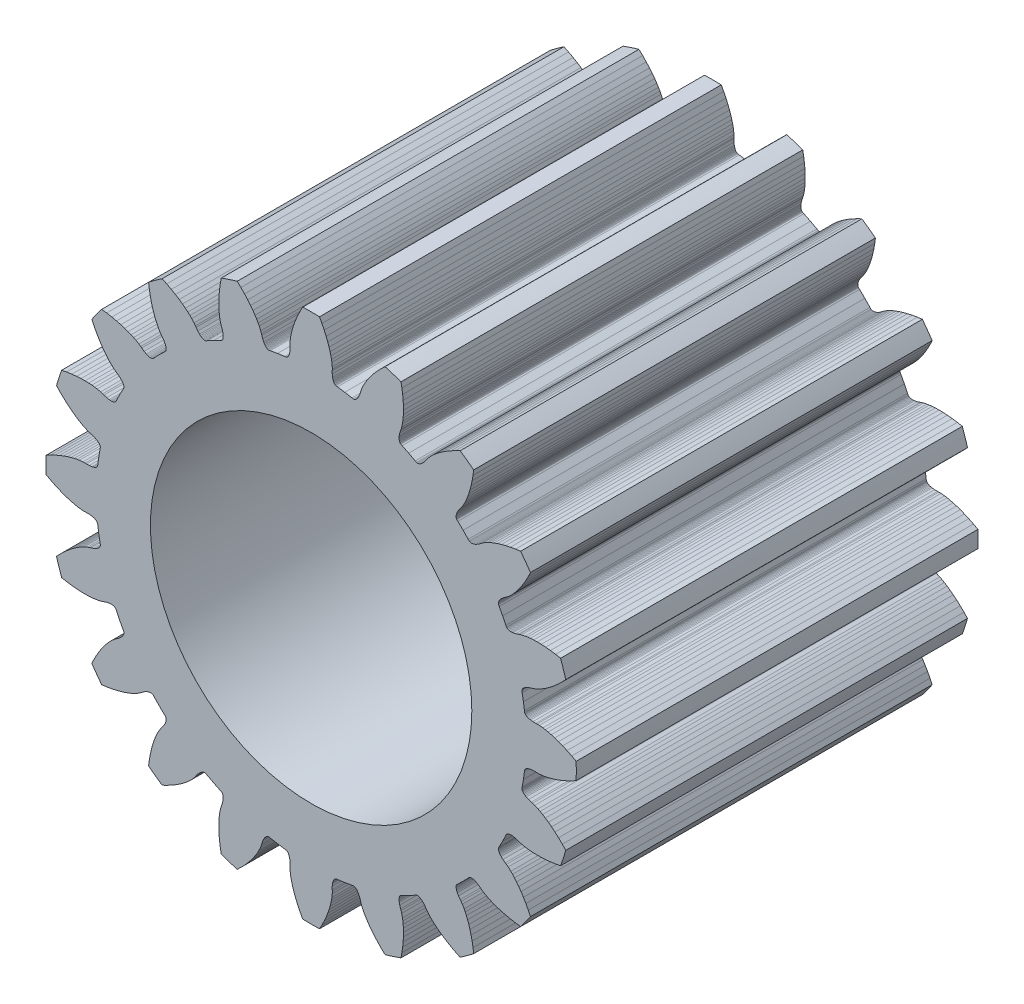
SolidWorks part; units mm, degrees
ref_plane "Front Plane" through (0, 0, 0) normal (0, 0, 1) x (1, 0, 0)
ref_plane "Top Plane" through (0, 0, 0) normal (0, 1, 0) x (1, 0, 0)
ref_plane "Right Plane" through (0, 0, 0) normal (1, 0, 0) x (0, 0, -1)
sketch "Model" plane through (0, 0, 0) normal (0, 0, 1) x (1, 0, 0)
  line L0 (6.2512, 1.7487) -> (6.1583, 1.6585)
  line L1 (6.1583, 1.6585) -> (6.069, 1.5788)
  line L2 (6.069, 1.5788) -> (5.984, 1.5091)
  line L3 (5.984, 1.5091) -> (5.9044, 1.4492)
  line L4 (5.9044, 1.4492) -> (5.8301, 1.398)
  line L5 (5.8301, 1.398) -> (5.762, 1.3551)
  line L6 (5.762, 1.3551) -> (5.7005, 1.3199)
  line L7 (5.7005, 1.3199) -> (5.6467, 1.292)
  line L8 (5.6467, 1.292) -> (5.5645, 1.2555)
  line L9 (5.5645, 1.2555) -> (5.5129, 1.2375)
  line L10 (5.5129, 1.2375) -> (5.4809, 1.2288)
  line L11 (5.4809, 1.2288) -> (5.4128, 1.2062)
  line L12 (5.4128, 1.2062) -> (5.3562, 1.1805)
  line L13 (5.3562, 1.1805) -> (5.3323, 1.1668)
  line L14 (5.3323, 1.1668) -> (5.3113, 1.1526)
  line L15 (5.3113, 1.1526) -> (5.2933, 1.1382)
  line L16 (5.2933, 1.1382) -> (5.2781, 1.1235)
  line L17 (5.2781, 1.1235) -> (5.2659, 1.1087)
  line L18 (5.2659, 1.1087) -> (5.2566, 1.094)
  line L19 (5.2566, 1.094) -> (5.2503, 1.0794)
  line L20 (5.2503, 1.0794) -> (5.2468, 1.0651)
  line L21 (5.2468, 1.0651) -> (5.2463, 1.0512)
  line L22 (5.2463, 1.0512) -> (5.2525, 1.0168)
  line L23 (5.2525, 1.0168) -> (5.2841, 0.8369)
  line L24 (5.2841, 0.8369) -> (5.3096, 0.656)
  line L25 (5.3096, 0.656) -> (5.3144, 0.6214)
  line L26 (5.3144, 0.6214) -> (5.3192, 0.6083)
  line L27 (5.3192, 0.6083) -> (5.3269, 0.5958)
  line L28 (5.3269, 0.5958) -> (5.3374, 0.5839)
  line L29 (5.3374, 0.5839) -> (5.3508, 0.5728)
  line L30 (5.3508, 0.5728) -> (5.367, 0.5625)
  line L31 (5.367, 0.5625) -> (5.3859, 0.5533)
  line L32 (5.3859, 0.5533) -> (5.4076, 0.5451)
  line L33 (5.4076, 0.5451) -> (5.4319, 0.5381)
  line L34 (5.4319, 0.5381) -> (5.4589, 0.5324)
  line L35 (5.4589, 0.5324) -> (5.5207, 0.5255)
  line L36 (5.5207, 0.5255) -> (5.5924, 0.525)
  line L37 (5.5924, 0.525) -> (5.6255, 0.5267)
  line L38 (5.6255, 0.5267) -> (5.6801, 0.5255)
  line L39 (5.6801, 0.5255) -> (5.7696, 0.5161)
  line L40 (5.7696, 0.5161) -> (5.8294, 0.5063)
  line L41 (5.8294, 0.5063) -> (5.8988, 0.4918)
  line L42 (5.8988, 0.4918) -> (5.9768, 0.4721)
  line L43 (5.9768, 0.4721) -> (6.0633, 0.4463)
  line L44 (6.0633, 0.4463) -> (6.1575, 0.4139)
  line L45 (6.1575, 0.4139) -> (6.2598, 0.3739)
  line L46 (6.2598, 0.3739) -> (6.3694, 0.3257)
  line L47 (6.3694, 0.3257) -> (6.4856, 0.2686)
  line L48 (6.4856, 0.2686) -> (6.5967, 0.2084)
  line L49 (6.5967, -0.2084) -> (6.4856, -0.2686)
  line L50 (6.4856, -0.2686) -> (6.3694, -0.3257)
  line L51 (6.3694, -0.3257) -> (6.2598, -0.3739)
  line L52 (6.2598, -0.3739) -> (6.1575, -0.4139)
  line L53 (6.1575, -0.4139) -> (6.0633, -0.4463)
  line L54 (6.0633, -0.4463) -> (5.9768, -0.4721)
  line L55 (5.9768, -0.4721) -> (5.8988, -0.4918)
  line L56 (5.8988, -0.4918) -> (5.8294, -0.5063)
  line L57 (5.8294, -0.5063) -> (5.7696, -0.5161)
  line L58 (5.7696, -0.5161) -> (5.6801, -0.5255)
  line L59 (5.6801, -0.5255) -> (5.6255, -0.5267)
  line L60 (5.6255, -0.5267) -> (5.5924, -0.525)
  line L61 (5.5924, -0.525) -> (5.5207, -0.5255)
  line L62 (5.5207, -0.5255) -> (5.4589, -0.5324)
  line L63 (5.4589, -0.5324) -> (5.4319, -0.5381)
  line L64 (5.4319, -0.5381) -> (5.4076, -0.5451)
  line L65 (5.4076, -0.5451) -> (5.3859, -0.5533)
  line L66 (5.3859, -0.5533) -> (5.367, -0.5625)
  line L67 (5.367, -0.5625) -> (5.3508, -0.5728)
  line L68 (5.3508, -0.5728) -> (5.3374, -0.5839)
  line L69 (5.3374, -0.5839) -> (5.3269, -0.5958)
  line L70 (5.3269, -0.5958) -> (5.3192, -0.6083)
  line L71 (5.3192, -0.6083) -> (5.3144, -0.6214)
  line L72 (5.3144, -0.6214) -> (5.3096, -0.656)
  line L73 (5.3096, -0.656) -> (5.2841, -0.8369)
  line L74 (5.2841, -0.8369) -> (5.2525, -1.0168)
  line L75 (5.2525, -1.0168) -> (5.2463, -1.0512)
  line L76 (5.2463, -1.0512) -> (5.2468, -1.0651)
  line L77 (5.2468, -1.0651) -> (5.2503, -1.0794)
  line L78 (5.2503, -1.0794) -> (5.2566, -1.094)
  line L79 (5.2566, -1.094) -> (5.2659, -1.1087)
  line L80 (5.2659, -1.1087) -> (5.2781, -1.1235)
  line L81 (5.2781, -1.1235) -> (5.2933, -1.1382)
  line L82 (5.2933, -1.1382) -> (5.3113, -1.1526)
  line L83 (5.3113, -1.1526) -> (5.3323, -1.1668)
  line L84 (5.3323, -1.1668) -> (5.3562, -1.1805)
  line L85 (5.3562, -1.1805) -> (5.4128, -1.2062)
  line L86 (5.4128, -1.2062) -> (5.4809, -1.2288)
  line L87 (5.4809, -1.2288) -> (5.5129, -1.2375)
  line L88 (5.5129, -1.2375) -> (5.5645, -1.2555)
  line L89 (5.5645, -1.2555) -> (5.6467, -1.292)
  line L90 (5.6467, -1.292) -> (5.7005, -1.3199)
  line L91 (5.7005, -1.3199) -> (5.762, -1.3551)
  line L92 (5.762, -1.3551) -> (5.8301, -1.398)
  line L93 (5.8301, -1.398) -> (5.9044, -1.4492)
  line L94 (5.9044, -1.4492) -> (5.984, -1.5091)
  line L95 (5.984, -1.5091) -> (6.069, -1.5788)
  line L96 (6.069, -1.5788) -> (6.1583, -1.6585)
  line L97 (6.1583, -1.6585) -> (6.2512, -1.7487)
  line L98 (6.2512, -1.7487) -> (6.3382, -1.8403)
  line L99 (6.2094, -2.2367) -> (6.0851, -2.2596)
  line L100 (6.0851, -2.2596) -> (5.957, -2.278)
  line L101 (5.957, -2.278) -> (5.8379, -2.29)
  line L102 (5.8379, -2.29) -> (5.7282, -2.2964)
  line L103 (5.7282, -2.2964) -> (5.6286, -2.2981)
  line L104 (5.6286, -2.2981) -> (5.5384, -2.2959)
  line L105 (5.5384, -2.2959) -> (5.4581, -2.2905)
  line L106 (5.4581, -2.2905) -> (5.3876, -2.2829)
  line L107 (5.3876, -2.2829) -> (5.3277, -2.2738)
  line L108 (5.3277, -2.2738) -> (5.2397, -2.255)
  line L109 (5.2397, -2.255) -> (5.1874, -2.2393)
  line L110 (5.1874, -2.2393) -> (5.1565, -2.2275)
  line L111 (5.1565, -2.2275) -> (5.0881, -2.2057)
  line L112 (5.0881, -2.2057) -> (5.0272, -2.1933)
  line L113 (5.0272, -2.1933) -> (4.9998, -2.1903)
  line L114 (4.9998, -2.1903) -> (4.9745, -2.1894)
  line L115 (4.9745, -2.1894) -> (4.9513, -2.1905)
  line L116 (4.9513, -2.1905) -> (4.9305, -2.1935)
  line L117 (4.9305, -2.1935) -> (4.9119, -2.1983)
  line L118 (4.9119, -2.1983) -> (4.8958, -2.2047)
  line L119 (4.8958, -2.2047) -> (4.8821, -2.2128)
  line L120 (4.8821, -2.2128) -> (4.8709, -2.2223)
  line L121 (4.8709, -2.2223) -> (4.8622, -2.2332)
  line L122 (4.8622, -2.2332) -> (4.847, -2.2647)
  line L123 (4.847, -2.2647) -> (4.7669, -2.4288)
  line L124 (4.7669, -2.4288) -> (4.6812, -2.5902)
  line L125 (4.6812, -2.5902) -> (4.6647, -2.621)
  line L126 (4.6647, -2.621) -> (4.6609, -2.6344)
  line L127 (4.6609, -2.6344) -> (4.6598, -2.649)
  line L128 (4.6598, -2.649) -> (4.6613, -2.6649)
  line L129 (4.6613, -2.6649) -> (4.6656, -2.6817)
  line L130 (4.6656, -2.6817) -> (4.6726, -2.6995)
  line L131 (4.6726, -2.6995) -> (4.6825, -2.7182)
  line L132 (4.6825, -2.7182) -> (4.6952, -2.7375)
  line L133 (4.6952, -2.7375) -> (4.7108, -2.7575)
  line L134 (4.7108, -2.7575) -> (4.7293, -2.7779)
  line L135 (4.7293, -2.7779) -> (4.7752, -2.8199)
  line L136 (4.7752, -2.8199) -> (4.8329, -2.8624)
  line L137 (4.8329, -2.8624) -> (4.8607, -2.8805)
  line L138 (4.8607, -2.8805) -> (4.9042, -2.9135)
  line L139 (4.9042, -2.9135) -> (4.9711, -2.9737)
  line L140 (4.9711, -2.9737) -> (5.0136, -3.0168)
  line L141 (5.0136, -3.0168) -> (5.0613, -3.0694)
  line L142 (5.0613, -3.0694) -> (5.1128, -3.1312)
  line L143 (5.1128, -3.1312) -> (5.1676, -3.2028)
  line L144 (5.1676, -3.2028) -> (5.2248, -3.2844)
  line L145 (5.2248, -3.2844) -> (5.2841, -3.3769)
  line L146 (5.2841, -3.3769) -> (5.3444, -3.4804)
  line L147 (5.3444, -3.4804) -> (5.4048, -3.5948)
  line L148 (5.4048, -3.5948) -> (5.4593, -3.7089)
  line L149 (5.2144, -4.046) -> (5.0891, -4.0294)
  line L150 (5.0891, -4.0294) -> (4.9615, -4.0073)
  line L151 (4.9615, -4.0073) -> (4.8445, -3.9819)
  line L152 (4.8445, -3.9819) -> (4.7382, -3.9541)
  line L153 (4.7382, -3.9541) -> (4.643, -3.925)
  line L154 (4.643, -3.925) -> (4.5579, -3.895)
  line L155 (4.5579, -3.895) -> (4.4831, -3.8651)
  line L156 (4.4831, -3.8651) -> (4.4185, -3.836)
  line L157 (4.4185, -3.836) -> (4.3643, -3.8088)
  line L158 (4.3643, -3.8088) -> (4.2864, -3.7638)
  line L159 (4.2864, -3.7638) -> (4.2415, -3.7327)
  line L160 (4.2415, -3.7327) -> (4.2158, -3.7119)
  line L161 (4.2158, -3.7119) -> (4.1575, -3.6701)
  line L162 (4.1575, -3.6701) -> (4.1034, -3.6394)
  line L163 (4.1034, -3.6394) -> (4.0782, -3.6281)
  line L164 (4.0782, -3.6281) -> (4.0544, -3.6195)
  line L165 (4.0544, -3.6195) -> (4.0321, -3.6134)
  line L166 (4.0321, -3.6134) -> (4.0113, -3.6097)
  line L167 (4.0113, -3.6097) -> (3.9922, -3.6085)
  line L168 (3.9922, -3.6085) -> (3.9748, -3.6097)
  line L169 (3.9748, -3.6097) -> (3.9593, -3.6131)
  line L170 (3.9593, -3.6131) -> (3.9457, -3.6187)
  line L171 (3.9457, -3.6187) -> (3.9342, -3.6264)
  line L172 (3.9342, -3.6264) -> (3.91, -3.6517)
  line L173 (3.91, -3.6517) -> (3.783, -3.783)
  line L174 (3.783, -3.783) -> (3.6517, -3.91)
  line L175 (3.6517, -3.91) -> (3.6264, -3.9342)
  line L176 (3.6264, -3.9342) -> (3.6187, -3.9457)
  line L177 (3.6187, -3.9457) -> (3.6131, -3.9593)
  line L178 (3.6131, -3.9593) -> (3.6097, -3.9748)
  line L179 (3.6097, -3.9748) -> (3.6085, -3.9922)
  line L180 (3.6085, -3.9922) -> (3.6097, -4.0113)
  line L181 (3.6097, -4.0113) -> (3.6134, -4.0321)
  line L182 (3.6134, -4.0321) -> (3.6195, -4.0544)
  line L183 (3.6195, -4.0544) -> (3.6281, -4.0782)
  line L184 (3.6281, -4.0782) -> (3.6394, -4.1034)
  line L185 (3.6394, -4.1034) -> (3.6701, -4.1575)
  line L186 (3.6701, -4.1575) -> (3.7119, -4.2158)
  line L187 (3.7119, -4.2158) -> (3.7327, -4.2415)
  line L188 (3.7327, -4.2415) -> (3.7638, -4.2864)
  line L189 (3.7638, -4.2864) -> (3.8088, -4.3643)
  line L190 (3.8088, -4.3643) -> (3.836, -4.4185)
  line L191 (3.836, -4.4185) -> (3.8651, -4.4831)
  line L192 (3.8651, -4.4831) -> (3.895, -4.5579)
  line L193 (3.895, -4.5579) -> (3.925, -4.643)
  line L194 (3.925, -4.643) -> (3.9541, -4.7382)
  line L195 (3.9541, -4.7382) -> (3.9819, -4.8445)
  line L196 (3.9819, -4.8445) -> (4.0073, -4.9615)
  line L197 (4.0073, -4.9615) -> (4.0294, -5.0891)
  line L198 (4.0294, -5.0891) -> (4.046, -5.2144)
  line L199 (3.7089, -5.4593) -> (3.5948, -5.4048)
  line L200 (3.5948, -5.4048) -> (3.4804, -5.3444)
  line L201 (3.4804, -5.3444) -> (3.3769, -5.2841)
  line L202 (3.3769, -5.2841) -> (3.2844, -5.2248)
  line L203 (3.2844, -5.2248) -> (3.2028, -5.1676)
  line L204 (3.2028, -5.1676) -> (3.1312, -5.1128)
  line L205 (3.1312, -5.1128) -> (3.0694, -5.0613)
  line L206 (3.0694, -5.0613) -> (3.0168, -5.0136)
  line L207 (3.0168, -5.0136) -> (2.9737, -4.9711)
  line L208 (2.9737, -4.9711) -> (2.9135, -4.9042)
  line L209 (2.9135, -4.9042) -> (2.8805, -4.8607)
  line L210 (2.8805, -4.8607) -> (2.8624, -4.8329)
  line L211 (2.8624, -4.8329) -> (2.8199, -4.7752)
  line L212 (2.8199, -4.7752) -> (2.7779, -4.7293)
  line L213 (2.7779, -4.7293) -> (2.7575, -4.7108)
  line L214 (2.7575, -4.7108) -> (2.7375, -4.6952)
  line L215 (2.7375, -4.6952) -> (2.7182, -4.6825)
  line L216 (2.7182, -4.6825) -> (2.6995, -4.6726)
  line L217 (2.6995, -4.6726) -> (2.6817, -4.6656)
  line L218 (2.6817, -4.6656) -> (2.6649, -4.6613)
  line L219 (2.6649, -4.6613) -> (2.649, -4.6598)
  line L220 (2.649, -4.6598) -> (2.6344, -4.6609)
  line L221 (2.6344, -4.6609) -> (2.621, -4.6647)
  line L222 (2.621, -4.6647) -> (2.5902, -4.6812)
  line L223 (2.5902, -4.6812) -> (2.4288, -4.7669)
  line L224 (2.4288, -4.7669) -> (2.2647, -4.847)
  line L225 (2.2647, -4.847) -> (2.2332, -4.8622)
  line L226 (2.2332, -4.8622) -> (2.2223, -4.8709)
  line L227 (2.2223, -4.8709) -> (2.2128, -4.8821)
  line L228 (2.2128, -4.8821) -> (2.2047, -4.8958)
  line L229 (2.2047, -4.8958) -> (2.1983, -4.9119)
  line L230 (2.1983, -4.9119) -> (2.1935, -4.9305)
  line L231 (2.1935, -4.9305) -> (2.1905, -4.9513)
  line L232 (2.1905, -4.9513) -> (2.1894, -4.9745)
  line L233 (2.1894, -4.9745) -> (2.1903, -4.9998)
  line L234 (2.1903, -4.9998) -> (2.1933, -5.0272)
  line L235 (2.1933, -5.0272) -> (2.2057, -5.0881)
  line L236 (2.2057, -5.0881) -> (2.2275, -5.1565)
  line L237 (2.2275, -5.1565) -> (2.2393, -5.1874)
  line L238 (2.2393, -5.1874) -> (2.255, -5.2397)
  line L239 (2.255, -5.2397) -> (2.2738, -5.3277)
  line L240 (2.2738, -5.3277) -> (2.2829, -5.3876)
  line L241 (2.2829, -5.3876) -> (2.2905, -5.4581)
  line L242 (2.2905, -5.4581) -> (2.2959, -5.5384)
  line L243 (2.2959, -5.5384) -> (2.2981, -5.6286)
  line L244 (2.2981, -5.6286) -> (2.2964, -5.7282)
  line L245 (2.2964, -5.7282) -> (2.29, -5.8379)
  line L246 (2.29, -5.8379) -> (2.278, -5.957)
  line L247 (2.278, -5.957) -> (2.2596, -6.0851)
  line L248 (2.2596, -6.0851) -> (2.2367, -6.2094)
  line L249 (1.8403, -6.3382) -> (1.7487, -6.2512)
  line L250 (1.7487, -6.2512) -> (1.6585, -6.1583)
  line L251 (1.6585, -6.1583) -> (1.5788, -6.069)
  line L252 (1.5788, -6.069) -> (1.5091, -5.984)
  line L253 (1.5091, -5.984) -> (1.4492, -5.9044)
  line L254 (1.4492, -5.9044) -> (1.398, -5.8301)
  line L255 (1.398, -5.8301) -> (1.3551, -5.762)
  line L256 (1.3551, -5.762) -> (1.3199, -5.7005)
  line L257 (1.3199, -5.7005) -> (1.292, -5.6467)
  line L258 (1.292, -5.6467) -> (1.2555, -5.5645)
  line L259 (1.2555, -5.5645) -> (1.2375, -5.5129)
  line L260 (1.2375, -5.5129) -> (1.2288, -5.4809)
  line L261 (1.2288, -5.4809) -> (1.2062, -5.4128)
  line L262 (1.2062, -5.4128) -> (1.1805, -5.3562)
  line L263 (1.1805, -5.3562) -> (1.1668, -5.3323)
  line L264 (1.1668, -5.3323) -> (1.1526, -5.3113)
  line L265 (1.1526, -5.3113) -> (1.1382, -5.2933)
  line L266 (1.1382, -5.2933) -> (1.1235, -5.2781)
  line L267 (1.1235, -5.2781) -> (1.1087, -5.2659)
  line L268 (1.1087, -5.2659) -> (1.094, -5.2566)
  line L269 (1.094, -5.2566) -> (1.0794, -5.2503)
  line L270 (1.0794, -5.2503) -> (1.0651, -5.2468)
  line L271 (1.0651, -5.2468) -> (1.0512, -5.2463)
  line L272 (1.0512, -5.2463) -> (1.0168, -5.2525)
  line L273 (1.0168, -5.2525) -> (0.8369, -5.2841)
  line L274 (0.8369, -5.2841) -> (0.656, -5.3096)
  line L275 (0.656, -5.3096) -> (0.6214, -5.3144)
  line L276 (0.6214, -5.3144) -> (0.6083, -5.3192)
  line L277 (0.6083, -5.3192) -> (0.5958, -5.3269)
  line L278 (0.5958, -5.3269) -> (0.5839, -5.3374)
  line L279 (0.5839, -5.3374) -> (0.5728, -5.3508)
  line L280 (0.5728, -5.3508) -> (0.5625, -5.367)
  line L281 (0.5625, -5.367) -> (0.5533, -5.3859)
  line L282 (0.5533, -5.3859) -> (0.5451, -5.4076)
  line L283 (0.5451, -5.4076) -> (0.5381, -5.4319)
  line L284 (0.5381, -5.4319) -> (0.5324, -5.4589)
  line L285 (0.5324, -5.4589) -> (0.5255, -5.5207)
  line L286 (0.5255, -5.5207) -> (0.525, -5.5924)
  line L287 (0.525, -5.5924) -> (0.5267, -5.6255)
  line L288 (0.5267, -5.6255) -> (0.5255, -5.6801)
  line L289 (0.5255, -5.6801) -> (0.5161, -5.7696)
  line L290 (0.5161, -5.7696) -> (0.5063, -5.8294)
  line L291 (0.5063, -5.8294) -> (0.4918, -5.8988)
  line L292 (0.4918, -5.8988) -> (0.4721, -5.9768)
  line L293 (0.4721, -5.9768) -> (0.4463, -6.0633)
  line L294 (0.4463, -6.0633) -> (0.4139, -6.1575)
  line L295 (0.4139, -6.1575) -> (0.3739, -6.2598)
  line L296 (0.3739, -6.2598) -> (0.3257, -6.3694)
  line L297 (0.3257, -6.3694) -> (0.2686, -6.4856)
  line L298 (0.2686, -6.4856) -> (0.2084, -6.5967)
  line L299 (-0.2084, -6.5967) -> (-0.2686, -6.4856)
  line L300 (-0.2686, -6.4856) -> (-0.3257, -6.3694)
  line L301 (-0.3257, -6.3694) -> (-0.3739, -6.2598)
  line L302 (-0.3739, -6.2598) -> (-0.4139, -6.1575)
  line L303 (-0.4139, -6.1575) -> (-0.4463, -6.0633)
  line L304 (-0.4463, -6.0633) -> (-0.4721, -5.9768)
  line L305 (-0.4721, -5.9768) -> (-0.4918, -5.8988)
  line L306 (-0.4918, -5.8988) -> (-0.5063, -5.8294)
  line L307 (-0.5063, -5.8294) -> (-0.5161, -5.7696)
  line L308 (-0.5161, -5.7696) -> (-0.5255, -5.6801)
  line L309 (-0.5255, -5.6801) -> (-0.5267, -5.6255)
  line L310 (-0.5267, -5.6255) -> (-0.525, -5.5924)
  line L311 (-0.525, -5.5924) -> (-0.5255, -5.5207)
  line L312 (-0.5255, -5.5207) -> (-0.5324, -5.4589)
  line L313 (-0.5324, -5.4589) -> (-0.5381, -5.4319)
  line L314 (-0.5381, -5.4319) -> (-0.5451, -5.4076)
  line L315 (-0.5451, -5.4076) -> (-0.5533, -5.3859)
  line L316 (-0.5533, -5.3859) -> (-0.5625, -5.367)
  line L317 (-0.5625, -5.367) -> (-0.5728, -5.3508)
  line L318 (-0.5728, -5.3508) -> (-0.5839, -5.3374)
  line L319 (-0.5839, -5.3374) -> (-0.5958, -5.3269)
  line L320 (-0.5958, -5.3269) -> (-0.6083, -5.3192)
  line L321 (-0.6083, -5.3192) -> (-0.6214, -5.3144)
  line L322 (-0.6214, -5.3144) -> (-0.656, -5.3096)
  line L323 (-0.656, -5.3096) -> (-0.8369, -5.2841)
  line L324 (-0.8369, -5.2841) -> (-1.0168, -5.2525)
  line L325 (-1.0168, -5.2525) -> (-1.0512, -5.2463)
  line L326 (-1.0512, -5.2463) -> (-1.0651, -5.2468)
  line L327 (-1.0651, -5.2468) -> (-1.0794, -5.2503)
  line L328 (-1.0794, -5.2503) -> (-1.094, -5.2566)
  line L329 (-1.094, -5.2566) -> (-1.1087, -5.2659)
  line L330 (-1.1087, -5.2659) -> (-1.1235, -5.2781)
  line L331 (-1.1235, -5.2781) -> (-1.1382, -5.2933)
  line L332 (-1.1382, -5.2933) -> (-1.1526, -5.3113)
  line L333 (-1.1526, -5.3113) -> (-1.1668, -5.3323)
  line L334 (-1.1668, -5.3323) -> (-1.1805, -5.3562)
  line L335 (-1.1805, -5.3562) -> (-1.2062, -5.4128)
  line L336 (-1.2062, -5.4128) -> (-1.2288, -5.4809)
  line L337 (-1.2288, -5.4809) -> (-1.2375, -5.5129)
  line L338 (-1.2375, -5.5129) -> (-1.2555, -5.5645)
  line L339 (-1.2555, -5.5645) -> (-1.292, -5.6467)
  line L340 (-1.292, -5.6467) -> (-1.3199, -5.7005)
  line L341 (-1.3199, -5.7005) -> (-1.3551, -5.762)
  line L342 (-1.3551, -5.762) -> (-1.398, -5.8301)
  line L343 (-1.398, -5.8301) -> (-1.4492, -5.9044)
  line L344 (-1.4492, -5.9044) -> (-1.5091, -5.984)
  line L345 (-1.5091, -5.984) -> (-1.5788, -6.069)
  line L346 (-1.5788, -6.069) -> (-1.6585, -6.1583)
  line L347 (-1.6585, -6.1583) -> (-1.7487, -6.2512)
  line L348 (-1.7487, -6.2512) -> (-1.8403, -6.3382)
  line L349 (-2.2367, -6.2094) -> (-2.2596, -6.0851)
  line L350 (-2.2596, -6.0851) -> (-2.278, -5.957)
  line L351 (-2.278, -5.957) -> (-2.29, -5.8379)
  line L352 (-2.29, -5.8379) -> (-2.2964, -5.7282)
  line L353 (-2.2964, -5.7282) -> (-2.2981, -5.6286)
  line L354 (-2.2981, -5.6286) -> (-2.2959, -5.5384)
  line L355 (-2.2959, -5.5384) -> (-2.2905, -5.4581)
  line L356 (-2.2905, -5.4581) -> (-2.2829, -5.3876)
  line L357 (-2.2829, -5.3876) -> (-2.2738, -5.3277)
  line L358 (-2.2738, -5.3277) -> (-2.255, -5.2397)
  line L359 (-2.255, -5.2397) -> (-2.2393, -5.1874)
  line L360 (-2.2393, -5.1874) -> (-2.2275, -5.1565)
  line L361 (-2.2275, -5.1565) -> (-2.2057, -5.0881)
  line L362 (-2.2057, -5.0881) -> (-2.1933, -5.0272)
  line L363 (-2.1933, -5.0272) -> (-2.1903, -4.9998)
  line L364 (-2.1903, -4.9998) -> (-2.1894, -4.9745)
  line L365 (-2.1894, -4.9745) -> (-2.1905, -4.9513)
  line L366 (-2.1905, -4.9513) -> (-2.1935, -4.9305)
  line L367 (-2.1935, -4.9305) -> (-2.1983, -4.9119)
  line L368 (-2.1983, -4.9119) -> (-2.2047, -4.8958)
  line L369 (-2.2047, -4.8958) -> (-2.2128, -4.8821)
  line L370 (-2.2128, -4.8821) -> (-2.2223, -4.8709)
  line L371 (-2.2223, -4.8709) -> (-2.2332, -4.8622)
  line L372 (-2.2332, -4.8622) -> (-2.2647, -4.847)
  line L373 (-2.2647, -4.847) -> (-2.4288, -4.7669)
  line L374 (-2.4288, -4.7669) -> (-2.5902, -4.6812)
  line L375 (-2.5902, -4.6812) -> (-2.621, -4.6647)
  line L376 (-2.621, -4.6647) -> (-2.6344, -4.6609)
  line L377 (-2.6344, -4.6609) -> (-2.649, -4.6598)
  line L378 (-2.649, -4.6598) -> (-2.6649, -4.6613)
  line L379 (-2.6649, -4.6613) -> (-2.6817, -4.6656)
  line L380 (-2.6817, -4.6656) -> (-2.6995, -4.6726)
  line L381 (-2.6995, -4.6726) -> (-2.7182, -4.6825)
  line L382 (-2.7182, -4.6825) -> (-2.7375, -4.6952)
  line L383 (-2.7375, -4.6952) -> (-2.7575, -4.7108)
  line L384 (-2.7575, -4.7108) -> (-2.7779, -4.7293)
  line L385 (-2.7779, -4.7293) -> (-2.8199, -4.7752)
  line L386 (-2.8199, -4.7752) -> (-2.8624, -4.8329)
  line L387 (-2.8624, -4.8329) -> (-2.8805, -4.8607)
  line L388 (-2.8805, -4.8607) -> (-2.9135, -4.9042)
  line L389 (-2.9135, -4.9042) -> (-2.9737, -4.9711)
  line L390 (-2.9737, -4.9711) -> (-3.0168, -5.0136)
  line L391 (-3.0168, -5.0136) -> (-3.0694, -5.0613)
  line L392 (-3.0694, -5.0613) -> (-3.1312, -5.1128)
  line L393 (-3.1312, -5.1128) -> (-3.2028, -5.1676)
  line L394 (-3.2028, -5.1676) -> (-3.2844, -5.2248)
  line L395 (-3.2844, -5.2248) -> (-3.3769, -5.2841)
  line L396 (-3.3769, -5.2841) -> (-3.4804, -5.3444)
  line L397 (-3.4804, -5.3444) -> (-3.5948, -5.4048)
  line L398 (-3.5948, -5.4048) -> (-3.7089, -5.4593)
  line L399 (-4.046, -5.2144) -> (-4.0294, -5.0891)
  line L400 (-4.0294, -5.0891) -> (-4.0073, -4.9615)
  line L401 (-4.0073, -4.9615) -> (-3.9819, -4.8445)
  line L402 (-3.9819, -4.8445) -> (-3.9541, -4.7382)
  line L403 (-3.9541, -4.7382) -> (-3.925, -4.643)
  line L404 (-3.925, -4.643) -> (-3.895, -4.5579)
  line L405 (-3.895, -4.5579) -> (-3.8651, -4.4831)
  line L406 (-3.8651, -4.4831) -> (-3.836, -4.4185)
  line L407 (-3.836, -4.4185) -> (-3.8088, -4.3643)
  line L408 (-3.8088, -4.3643) -> (-3.7638, -4.2864)
  line L409 (-3.7638, -4.2864) -> (-3.7327, -4.2415)
  line L410 (-3.7327, -4.2415) -> (-3.7119, -4.2158)
  line L411 (-3.7119, -4.2158) -> (-3.6701, -4.1575)
  line L412 (-3.6701, -4.1575) -> (-3.6394, -4.1034)
  line L413 (-3.6394, -4.1034) -> (-3.6281, -4.0782)
  line L414 (-3.6281, -4.0782) -> (-3.6195, -4.0544)
  line L415 (-3.6195, -4.0544) -> (-3.6134, -4.0321)
  line L416 (-3.6134, -4.0321) -> (-3.6097, -4.0113)
  line L417 (-3.6097, -4.0113) -> (-3.6085, -3.9922)
  line L418 (-3.6085, -3.9922) -> (-3.6097, -3.9748)
  line L419 (-3.6097, -3.9748) -> (-3.6131, -3.9593)
  line L420 (-3.6131, -3.9593) -> (-3.6187, -3.9457)
  line L421 (-3.6187, -3.9457) -> (-3.6264, -3.9342)
  line L422 (-3.6264, -3.9342) -> (-3.6517, -3.91)
  line L423 (-3.6517, -3.91) -> (-3.783, -3.783)
  line L424 (-3.783, -3.783) -> (-3.91, -3.6517)
  line L425 (-3.91, -3.6517) -> (-3.9342, -3.6264)
  line L426 (-3.9342, -3.6264) -> (-3.9457, -3.6187)
  line L427 (-3.9457, -3.6187) -> (-3.9593, -3.6131)
  line L428 (-3.9593, -3.6131) -> (-3.9748, -3.6097)
  line L429 (-3.9748, -3.6097) -> (-3.9922, -3.6085)
  line L430 (-3.9922, -3.6085) -> (-4.0113, -3.6097)
  line L431 (-4.0113, -3.6097) -> (-4.0321, -3.6134)
  line L432 (-4.0321, -3.6134) -> (-4.0544, -3.6195)
  line L433 (-4.0544, -3.6195) -> (-4.0782, -3.6281)
  line L434 (-4.0782, -3.6281) -> (-4.1034, -3.6394)
  line L435 (-4.1034, -3.6394) -> (-4.1575, -3.6701)
  line L436 (-4.1575, -3.6701) -> (-4.2158, -3.7119)
  line L437 (-4.2158, -3.7119) -> (-4.2415, -3.7327)
  line L438 (-4.2415, -3.7327) -> (-4.2864, -3.7638)
  line L439 (-4.2864, -3.7638) -> (-4.3643, -3.8088)
  line L440 (-4.3643, -3.8088) -> (-4.4185, -3.836)
  line L441 (-4.4185, -3.836) -> (-4.4831, -3.8651)
  line L442 (-4.4831, -3.8651) -> (-4.5579, -3.895)
  line L443 (-4.5579, -3.895) -> (-4.643, -3.925)
  line L444 (-4.643, -3.925) -> (-4.7382, -3.9541)
  line L445 (-4.7382, -3.9541) -> (-4.8445, -3.9819)
  line L446 (-4.8445, -3.9819) -> (-4.9615, -4.0073)
  line L447 (-4.9615, -4.0073) -> (-5.0891, -4.0294)
  line L448 (-5.0891, -4.0294) -> (-5.2144, -4.046)
  line L449 (-5.4593, -3.7089) -> (-5.4048, -3.5948)
  line L450 (-5.4048, -3.5948) -> (-5.3444, -3.4804)
  line L451 (-5.3444, -3.4804) -> (-5.2841, -3.3769)
  line L452 (-5.2841, -3.3769) -> (-5.2248, -3.2844)
  line L453 (-5.2248, -3.2844) -> (-5.1676, -3.2028)
  line L454 (-5.1676, -3.2028) -> (-5.1128, -3.1312)
  line L455 (-5.1128, -3.1312) -> (-5.0613, -3.0694)
  line L456 (-5.0613, -3.0694) -> (-5.0136, -3.0168)
  line L457 (-5.0136, -3.0168) -> (-4.9711, -2.9737)
  line L458 (-4.9711, -2.9737) -> (-4.9042, -2.9135)
  line L459 (-4.9042, -2.9135) -> (-4.8607, -2.8805)
  line L460 (-4.8607, -2.8805) -> (-4.8329, -2.8624)
  line L461 (-4.8329, -2.8624) -> (-4.7752, -2.8199)
  line L462 (-4.7752, -2.8199) -> (-4.7293, -2.7779)
  line L463 (-4.7293, -2.7779) -> (-4.7108, -2.7575)
  line L464 (-4.7108, -2.7575) -> (-4.6952, -2.7375)
  line L465 (-4.6952, -2.7375) -> (-4.6825, -2.7182)
  line L466 (-4.6825, -2.7182) -> (-4.6726, -2.6995)
  line L467 (-4.6726, -2.6995) -> (-4.6656, -2.6817)
  line L468 (-4.6656, -2.6817) -> (-4.6613, -2.6649)
  line L469 (-4.6613, -2.6649) -> (-4.6598, -2.649)
  line L470 (-4.6598, -2.649) -> (-4.6609, -2.6344)
  line L471 (-4.6609, -2.6344) -> (-4.6647, -2.621)
  line L472 (-4.6647, -2.621) -> (-4.6812, -2.5902)
  line L473 (-4.6812, -2.5902) -> (-4.7669, -2.4288)
  line L474 (-4.7669, -2.4288) -> (-4.847, -2.2647)
  line L475 (-4.847, -2.2647) -> (-4.8622, -2.2332)
  line L476 (-4.8622, -2.2332) -> (-4.8709, -2.2223)
  line L477 (-4.8709, -2.2223) -> (-4.8821, -2.2128)
  line L478 (-4.8821, -2.2128) -> (-4.8958, -2.2047)
  line L479 (-4.8958, -2.2047) -> (-4.9119, -2.1983)
  line L480 (-4.9119, -2.1983) -> (-4.9305, -2.1935)
  line L481 (-4.9305, -2.1935) -> (-4.9513, -2.1905)
  line L482 (-4.9513, -2.1905) -> (-4.9745, -2.1894)
  line L483 (-4.9745, -2.1894) -> (-4.9998, -2.1903)
  line L484 (-4.9998, -2.1903) -> (-5.0272, -2.1933)
  line L485 (-5.0272, -2.1933) -> (-5.0881, -2.2057)
  line L486 (-5.0881, -2.2057) -> (-5.1565, -2.2275)
  line L487 (-5.1565, -2.2275) -> (-5.1874, -2.2393)
  line L488 (-5.1874, -2.2393) -> (-5.2397, -2.255)
  line L489 (-5.2397, -2.255) -> (-5.3277, -2.2738)
  line L490 (-5.3277, -2.2738) -> (-5.3876, -2.2829)
  line L491 (-5.3876, -2.2829) -> (-5.4581, -2.2905)
  line L492 (-5.4581, -2.2905) -> (-5.5384, -2.2959)
  line L493 (-5.5384, -2.2959) -> (-5.6286, -2.2981)
  line L494 (-5.6286, -2.2981) -> (-5.7282, -2.2964)
  line L495 (-5.7282, -2.2964) -> (-5.8379, -2.29)
  line L496 (-5.8379, -2.29) -> (-5.957, -2.278)
  line L497 (-5.957, -2.278) -> (-6.0851, -2.2596)
  line L498 (-6.0851, -2.2596) -> (-6.2094, -2.2367)
  line L499 (-6.3382, -1.8403) -> (-6.2512, -1.7487)
  line L500 (-6.2512, -1.7487) -> (-6.1583, -1.6585)
  line L501 (-6.1583, -1.6585) -> (-6.069, -1.5788)
  line L502 (-6.069, -1.5788) -> (-5.984, -1.5091)
  line L503 (-5.984, -1.5091) -> (-5.9044, -1.4492)
  line L504 (-5.9044, -1.4492) -> (-5.8301, -1.398)
  line L505 (-5.8301, -1.398) -> (-5.762, -1.3551)
  line L506 (-5.762, -1.3551) -> (-5.7005, -1.3199)
  line L507 (-5.7005, -1.3199) -> (-5.6467, -1.292)
  line L508 (-5.6467, -1.292) -> (-5.5645, -1.2555)
  line L509 (-5.5645, -1.2555) -> (-5.5129, -1.2375)
  line L510 (-5.5129, -1.2375) -> (-5.4809, -1.2288)
  line L511 (-5.4809, -1.2288) -> (-5.4128, -1.2062)
  line L512 (-5.4128, -1.2062) -> (-5.3562, -1.1805)
  line L513 (-5.3562, -1.1805) -> (-5.3323, -1.1668)
  line L514 (-5.3323, -1.1668) -> (-5.3113, -1.1526)
  line L515 (-5.3113, -1.1526) -> (-5.2933, -1.1382)
  line L516 (-5.2933, -1.1382) -> (-5.2781, -1.1235)
  line L517 (-5.2781, -1.1235) -> (-5.2659, -1.1087)
  line L518 (-5.2659, -1.1087) -> (-5.2566, -1.094)
  line L519 (-5.2566, -1.094) -> (-5.2503, -1.0794)
  line L520 (-5.2503, -1.0794) -> (-5.2468, -1.0651)
  line L521 (-5.2468, -1.0651) -> (-5.2463, -1.0512)
  line L522 (-5.2463, -1.0512) -> (-5.2525, -1.0168)
  line L523 (-5.2525, -1.0168) -> (-5.2841, -0.8369)
  line L524 (-5.2841, -0.8369) -> (-5.3096, -0.656)
  line L525 (-5.3096, -0.656) -> (-5.3144, -0.6214)
  line L526 (-5.3144, -0.6214) -> (-5.3192, -0.6083)
  line L527 (-5.3192, -0.6083) -> (-5.3269, -0.5958)
  line L528 (-5.3269, -0.5958) -> (-5.3374, -0.5839)
  line L529 (-5.3374, -0.5839) -> (-5.3508, -0.5728)
  line L530 (-5.3508, -0.5728) -> (-5.367, -0.5625)
  line L531 (-5.367, -0.5625) -> (-5.3859, -0.5533)
  line L532 (-5.3859, -0.5533) -> (-5.4076, -0.5451)
  line L533 (-5.4076, -0.5451) -> (-5.4319, -0.5381)
  line L534 (-5.4319, -0.5381) -> (-5.4589, -0.5324)
  line L535 (-5.4589, -0.5324) -> (-5.5207, -0.5255)
  line L536 (-5.5207, -0.5255) -> (-5.5924, -0.525)
  line L537 (-5.5924, -0.525) -> (-5.6255, -0.5267)
  line L538 (-5.6255, -0.5267) -> (-5.6801, -0.5255)
  line L539 (-5.6801, -0.5255) -> (-5.7696, -0.5161)
  line L540 (-5.7696, -0.5161) -> (-5.8294, -0.5063)
  line L541 (-5.8294, -0.5063) -> (-5.8988, -0.4918)
  line L542 (-5.8988, -0.4918) -> (-5.9768, -0.4721)
  line L543 (-5.9768, -0.4721) -> (-6.0633, -0.4463)
  line L544 (-6.0633, -0.4463) -> (-6.1575, -0.4139)
  line L545 (-6.1575, -0.4139) -> (-6.2598, -0.3739)
  line L546 (-6.2598, -0.3739) -> (-6.3694, -0.3257)
  line L547 (-6.3694, -0.3257) -> (-6.4856, -0.2686)
  line L548 (-6.4856, -0.2686) -> (-6.5967, -0.2084)
  line L549 (-6.5967, 0.2084) -> (-6.4856, 0.2686)
  line L550 (-6.4856, 0.2686) -> (-6.3694, 0.3257)
  line L551 (-6.3694, 0.3257) -> (-6.2598, 0.3739)
  line L552 (-6.2598, 0.3739) -> (-6.1575, 0.4139)
  line L553 (-6.1575, 0.4139) -> (-6.0633, 0.4463)
  line L554 (-6.0633, 0.4463) -> (-5.9768, 0.4721)
  line L555 (-5.9768, 0.4721) -> (-5.8988, 0.4918)
  line L556 (-5.8988, 0.4918) -> (-5.8294, 0.5063)
  line L557 (-5.8294, 0.5063) -> (-5.7696, 0.5161)
  line L558 (-5.7696, 0.5161) -> (-5.6801, 0.5255)
  line L559 (-5.6801, 0.5255) -> (-5.6255, 0.5267)
  line L560 (-5.6255, 0.5267) -> (-5.5924, 0.525)
  line L561 (-5.5924, 0.525) -> (-5.5207, 0.5255)
  line L562 (-5.5207, 0.5255) -> (-5.4589, 0.5324)
  line L563 (-5.4589, 0.5324) -> (-5.4319, 0.5381)
  line L564 (-5.4319, 0.5381) -> (-5.4076, 0.5451)
  line L565 (-5.4076, 0.5451) -> (-5.3859, 0.5533)
  line L566 (-5.3859, 0.5533) -> (-5.367, 0.5625)
  line L567 (-5.367, 0.5625) -> (-5.3508, 0.5728)
  line L568 (-5.3508, 0.5728) -> (-5.3374, 0.5839)
  line L569 (-5.3374, 0.5839) -> (-5.3269, 0.5958)
  line L570 (-5.3269, 0.5958) -> (-5.3192, 0.6083)
  line L571 (-5.3192, 0.6083) -> (-5.3144, 0.6214)
  line L572 (-5.3144, 0.6214) -> (-5.3096, 0.656)
  line L573 (-5.3096, 0.656) -> (-5.2841, 0.8369)
  line L574 (-5.2841, 0.8369) -> (-5.2525, 1.0168)
  line L575 (-5.2525, 1.0168) -> (-5.2463, 1.0512)
  line L576 (-5.2463, 1.0512) -> (-5.2468, 1.0651)
  line L577 (-5.2468, 1.0651) -> (-5.2503, 1.0794)
  line L578 (-5.2503, 1.0794) -> (-5.2566, 1.094)
  line L579 (-5.2566, 1.094) -> (-5.2659, 1.1087)
  line L580 (-5.2659, 1.1087) -> (-5.2781, 1.1235)
  line L581 (-5.2781, 1.1235) -> (-5.2933, 1.1382)
  line L582 (-5.2933, 1.1382) -> (-5.3113, 1.1526)
  line L583 (-5.3113, 1.1526) -> (-5.3323, 1.1668)
  line L584 (-5.3323, 1.1668) -> (-5.3562, 1.1805)
  line L585 (-5.3562, 1.1805) -> (-5.4128, 1.2062)
  line L586 (-5.4128, 1.2062) -> (-5.4809, 1.2288)
  line L587 (-5.4809, 1.2288) -> (-5.5129, 1.2375)
  line L588 (-5.5129, 1.2375) -> (-5.5645, 1.2555)
  line L589 (-5.5645, 1.2555) -> (-5.6467, 1.292)
  line L590 (-5.6467, 1.292) -> (-5.7005, 1.3199)
  line L591 (-5.7005, 1.3199) -> (-5.762, 1.3551)
  line L592 (-5.762, 1.3551) -> (-5.8301, 1.398)
  line L593 (-5.8301, 1.398) -> (-5.9044, 1.4492)
  line L594 (-5.9044, 1.4492) -> (-5.984, 1.5091)
  line L595 (-5.984, 1.5091) -> (-6.069, 1.5788)
  line L596 (-6.069, 1.5788) -> (-6.1583, 1.6585)
  line L597 (-6.1583, 1.6585) -> (-6.2512, 1.7487)
  line L598 (-6.2512, 1.7487) -> (-6.3382, 1.8403)
  line L599 (-6.2094, 2.2367) -> (-6.0851, 2.2596)
  line L600 (-6.0851, 2.2596) -> (-5.957, 2.278)
  line L601 (-5.957, 2.278) -> (-5.8379, 2.29)
  line L602 (-5.8379, 2.29) -> (-5.7282, 2.2964)
  line L603 (-5.7282, 2.2964) -> (-5.6286, 2.2981)
  line L604 (-5.6286, 2.2981) -> (-5.5384, 2.2959)
  line L605 (-5.5384, 2.2959) -> (-5.4581, 2.2905)
  line L606 (-5.4581, 2.2905) -> (-5.3876, 2.2829)
  line L607 (-5.3876, 2.2829) -> (-5.3277, 2.2738)
  line L608 (-5.3277, 2.2738) -> (-5.2397, 2.255)
  line L609 (-5.2397, 2.255) -> (-5.1874, 2.2393)
  line L610 (-5.1874, 2.2393) -> (-5.1565, 2.2275)
  line L611 (-5.1565, 2.2275) -> (-5.0881, 2.2057)
  line L612 (-5.0881, 2.2057) -> (-5.0272, 2.1933)
  line L613 (-5.0272, 2.1933) -> (-4.9998, 2.1903)
  line L614 (-4.9998, 2.1903) -> (-4.9745, 2.1894)
  line L615 (-4.9745, 2.1894) -> (-4.9513, 2.1905)
  line L616 (-4.9513, 2.1905) -> (-4.9305, 2.1935)
  line L617 (-4.9305, 2.1935) -> (-4.9119, 2.1983)
  line L618 (-4.9119, 2.1983) -> (-4.8958, 2.2047)
  line L619 (-4.8958, 2.2047) -> (-4.8821, 2.2128)
  line L620 (-4.8821, 2.2128) -> (-4.8709, 2.2223)
  line L621 (-4.8709, 2.2223) -> (-4.8622, 2.2332)
  line L622 (-4.8622, 2.2332) -> (-4.847, 2.2647)
  line L623 (-4.847, 2.2647) -> (-4.7669, 2.4288)
  line L624 (-4.7669, 2.4288) -> (-4.6812, 2.5902)
  line L625 (-4.6812, 2.5902) -> (-4.6647, 2.621)
  line L626 (-4.6647, 2.621) -> (-4.6609, 2.6344)
  line L627 (-4.6609, 2.6344) -> (-4.6598, 2.649)
  line L628 (-4.6598, 2.649) -> (-4.6613, 2.6649)
  line L629 (-4.6613, 2.6649) -> (-4.6656, 2.6817)
  line L630 (-4.6656, 2.6817) -> (-4.6726, 2.6995)
  line L631 (-4.6726, 2.6995) -> (-4.6825, 2.7182)
  line L632 (-4.6825, 2.7182) -> (-4.6952, 2.7375)
  line L633 (-4.6952, 2.7375) -> (-4.7108, 2.7575)
  line L634 (-4.7108, 2.7575) -> (-4.7293, 2.7779)
  line L635 (-4.7293, 2.7779) -> (-4.7752, 2.8199)
  line L636 (-4.7752, 2.8199) -> (-4.8329, 2.8624)
  line L637 (-4.8329, 2.8624) -> (-4.8607, 2.8805)
  line L638 (-4.8607, 2.8805) -> (-4.9042, 2.9135)
  line L639 (-4.9042, 2.9135) -> (-4.9711, 2.9737)
  line L640 (-4.9711, 2.9737) -> (-5.0136, 3.0168)
  line L641 (-5.0136, 3.0168) -> (-5.0613, 3.0694)
  line L642 (-5.0613, 3.0694) -> (-5.1128, 3.1312)
  line L643 (-5.1128, 3.1312) -> (-5.1676, 3.2028)
  line L644 (-5.1676, 3.2028) -> (-5.2248, 3.2844)
  line L645 (-5.2248, 3.2844) -> (-5.2841, 3.3769)
  line L646 (-5.2841, 3.3769) -> (-5.3444, 3.4804)
  line L647 (-5.3444, 3.4804) -> (-5.4048, 3.5948)
  line L648 (-5.4048, 3.5948) -> (-5.4593, 3.7089)
  line L649 (-5.2144, 4.046) -> (-5.0891, 4.0294)
  line L650 (-5.0891, 4.0294) -> (-4.9615, 4.0073)
  line L651 (-4.9615, 4.0073) -> (-4.8445, 3.9819)
  line L652 (-4.8445, 3.9819) -> (-4.7382, 3.9541)
  line L653 (-4.7382, 3.9541) -> (-4.643, 3.925)
  line L654 (-4.643, 3.925) -> (-4.5579, 3.895)
  line L655 (-4.5579, 3.895) -> (-4.4831, 3.8651)
  line L656 (-4.4831, 3.8651) -> (-4.4185, 3.836)
  line L657 (-4.4185, 3.836) -> (-4.3643, 3.8088)
  line L658 (-4.3643, 3.8088) -> (-4.2864, 3.7638)
  line L659 (-4.2864, 3.7638) -> (-4.2415, 3.7327)
  line L660 (-4.2415, 3.7327) -> (-4.2158, 3.7119)
  line L661 (-4.2158, 3.7119) -> (-4.1575, 3.6701)
  line L662 (-4.1575, 3.6701) -> (-4.1034, 3.6394)
  line L663 (-4.1034, 3.6394) -> (-4.0782, 3.6281)
  line L664 (-4.0782, 3.6281) -> (-4.0544, 3.6195)
  line L665 (-4.0544, 3.6195) -> (-4.0321, 3.6134)
  line L666 (-4.0321, 3.6134) -> (-4.0113, 3.6097)
  line L667 (-4.0113, 3.6097) -> (-3.9922, 3.6085)
  line L668 (-3.9922, 3.6085) -> (-3.9748, 3.6097)
  line L669 (-3.9748, 3.6097) -> (-3.9593, 3.6131)
  line L670 (-3.9593, 3.6131) -> (-3.9457, 3.6187)
  line L671 (-3.9457, 3.6187) -> (-3.9342, 3.6264)
  line L672 (-3.9342, 3.6264) -> (-3.91, 3.6517)
  line L673 (-3.91, 3.6517) -> (-3.783, 3.783)
  line L674 (-3.783, 3.783) -> (-3.6517, 3.91)
  line L675 (-3.6517, 3.91) -> (-3.6264, 3.9342)
  line L676 (-3.6264, 3.9342) -> (-3.6187, 3.9457)
  line L677 (-3.6187, 3.9457) -> (-3.6131, 3.9593)
  line L678 (-3.6131, 3.9593) -> (-3.6097, 3.9748)
  line L679 (-3.6097, 3.9748) -> (-3.6085, 3.9922)
  line L680 (-3.6085, 3.9922) -> (-3.6097, 4.0113)
  line L681 (-3.6097, 4.0113) -> (-3.6134, 4.0321)
  line L682 (-3.6134, 4.0321) -> (-3.6195, 4.0544)
  line L683 (-3.6195, 4.0544) -> (-3.6281, 4.0782)
  line L684 (-3.6281, 4.0782) -> (-3.6394, 4.1034)
  line L685 (-3.6394, 4.1034) -> (-3.6701, 4.1575)
  line L686 (-3.6701, 4.1575) -> (-3.7119, 4.2158)
  line L687 (-3.7119, 4.2158) -> (-3.7327, 4.2415)
  line L688 (-3.7327, 4.2415) -> (-3.7638, 4.2864)
  line L689 (-3.7638, 4.2864) -> (-3.8088, 4.3643)
  line L690 (-3.8088, 4.3643) -> (-3.836, 4.4185)
  line L691 (-3.836, 4.4185) -> (-3.8651, 4.4831)
  line L692 (-3.8651, 4.4831) -> (-3.895, 4.5579)
  line L693 (-3.895, 4.5579) -> (-3.925, 4.643)
  line L694 (-3.925, 4.643) -> (-3.9541, 4.7382)
  line L695 (-3.9541, 4.7382) -> (-3.9819, 4.8445)
  line L696 (-3.9819, 4.8445) -> (-4.0073, 4.9615)
  line L697 (-4.0073, 4.9615) -> (-4.0294, 5.0891)
  line L698 (-4.0294, 5.0891) -> (-4.046, 5.2144)
  line L699 (-3.7089, 5.4593) -> (-3.5948, 5.4048)
  line L700 (-3.5948, 5.4048) -> (-3.4804, 5.3444)
  line L701 (-3.4804, 5.3444) -> (-3.3769, 5.2841)
  line L702 (-3.3769, 5.2841) -> (-3.2844, 5.2248)
  line L703 (-3.2844, 5.2248) -> (-3.2028, 5.1676)
  line L704 (-3.2028, 5.1676) -> (-3.1312, 5.1128)
  line L705 (-3.1312, 5.1128) -> (-3.0694, 5.0613)
  line L706 (-3.0694, 5.0613) -> (-3.0168, 5.0136)
  line L707 (-3.0168, 5.0136) -> (-2.9737, 4.9711)
  line L708 (-2.9737, 4.9711) -> (-2.9135, 4.9042)
  line L709 (-2.9135, 4.9042) -> (-2.8805, 4.8607)
  line L710 (-2.8805, 4.8607) -> (-2.8624, 4.8329)
  line L711 (-2.8624, 4.8329) -> (-2.8199, 4.7752)
  line L712 (-2.8199, 4.7752) -> (-2.7779, 4.7293)
  line L713 (-2.7779, 4.7293) -> (-2.7575, 4.7108)
  line L714 (-2.7575, 4.7108) -> (-2.7375, 4.6952)
  line L715 (-2.7375, 4.6952) -> (-2.7182, 4.6825)
  line L716 (-2.7182, 4.6825) -> (-2.6995, 4.6726)
  line L717 (-2.6995, 4.6726) -> (-2.6817, 4.6656)
  line L718 (-2.6817, 4.6656) -> (-2.6649, 4.6613)
  line L719 (-2.6649, 4.6613) -> (-2.649, 4.6598)
  line L720 (-2.649, 4.6598) -> (-2.6344, 4.6609)
  line L721 (-2.6344, 4.6609) -> (-2.621, 4.6647)
  line L722 (-2.621, 4.6647) -> (-2.5902, 4.6812)
  line L723 (-2.5902, 4.6812) -> (-2.4288, 4.7669)
  line L724 (-2.4288, 4.7669) -> (-2.2647, 4.847)
  line L725 (-2.2647, 4.847) -> (-2.2332, 4.8622)
  line L726 (-2.2332, 4.8622) -> (-2.2223, 4.8709)
  line L727 (-2.2223, 4.8709) -> (-2.2128, 4.8821)
  line L728 (-2.2128, 4.8821) -> (-2.2047, 4.8958)
  line L729 (-2.2047, 4.8958) -> (-2.1983, 4.9119)
  line L730 (-2.1983, 4.9119) -> (-2.1935, 4.9305)
  line L731 (-2.1935, 4.9305) -> (-2.1905, 4.9513)
  line L732 (-2.1905, 4.9513) -> (-2.1894, 4.9745)
  line L733 (-2.1894, 4.9745) -> (-2.1903, 4.9998)
  line L734 (-2.1903, 4.9998) -> (-2.1933, 5.0272)
  line L735 (-2.1933, 5.0272) -> (-2.2057, 5.0881)
  line L736 (-2.2057, 5.0881) -> (-2.2275, 5.1565)
  line L737 (-2.2275, 5.1565) -> (-2.2393, 5.1874)
  line L738 (-2.2393, 5.1874) -> (-2.255, 5.2397)
  line L739 (-2.255, 5.2397) -> (-2.2738, 5.3277)
  line L740 (-2.2738, 5.3277) -> (-2.2829, 5.3876)
  line L741 (-2.2829, 5.3876) -> (-2.2905, 5.4581)
  line L742 (-2.2905, 5.4581) -> (-2.2959, 5.5384)
  line L743 (-2.2959, 5.5384) -> (-2.2981, 5.6286)
  line L744 (-2.2981, 5.6286) -> (-2.2964, 5.7282)
  line L745 (-2.2964, 5.7282) -> (-2.29, 5.8379)
  line L746 (-2.29, 5.8379) -> (-2.278, 5.957)
  line L747 (-2.278, 5.957) -> (-2.2596, 6.0851)
  line L748 (-2.2596, 6.0851) -> (-2.2367, 6.2094)
  line L749 (-1.8403, 6.3382) -> (-1.7487, 6.2512)
  line L750 (-1.7487, 6.2512) -> (-1.6585, 6.1583)
  line L751 (-1.6585, 6.1583) -> (-1.5788, 6.069)
  line L752 (-1.5788, 6.069) -> (-1.5091, 5.984)
  line L753 (-1.5091, 5.984) -> (-1.4492, 5.9044)
  line L754 (-1.4492, 5.9044) -> (-1.398, 5.8301)
  line L755 (-1.398, 5.8301) -> (-1.3551, 5.762)
  line L756 (-1.3551, 5.762) -> (-1.3199, 5.7005)
  line L757 (-1.3199, 5.7005) -> (-1.292, 5.6467)
  line L758 (-1.292, 5.6467) -> (-1.2555, 5.5645)
  line L759 (-1.2555, 5.5645) -> (-1.2375, 5.5129)
  line L760 (-1.2375, 5.5129) -> (-1.2288, 5.4809)
  line L761 (-1.2288, 5.4809) -> (-1.2062, 5.4128)
  line L762 (-1.2062, 5.4128) -> (-1.1805, 5.3562)
  line L763 (-1.1805, 5.3562) -> (-1.1668, 5.3323)
  line L764 (-1.1668, 5.3323) -> (-1.1526, 5.3113)
  line L765 (-1.1526, 5.3113) -> (-1.1382, 5.2933)
  line L766 (-1.1382, 5.2933) -> (-1.1235, 5.2781)
  line L767 (-1.1235, 5.2781) -> (-1.1087, 5.2659)
  line L768 (-1.1087, 5.2659) -> (-1.094, 5.2566)
  line L769 (-1.094, 5.2566) -> (-1.0794, 5.2503)
  line L770 (-1.0794, 5.2503) -> (-1.0651, 5.2468)
  line L771 (-1.0651, 5.2468) -> (-1.0512, 5.2463)
  line L772 (-1.0512, 5.2463) -> (-1.0168, 5.2525)
  line L773 (-1.0168, 5.2525) -> (-0.8369, 5.2841)
  line L774 (-0.8369, 5.2841) -> (-0.656, 5.3096)
  line L775 (-0.656, 5.3096) -> (-0.6214, 5.3144)
  line L776 (-0.6214, 5.3144) -> (-0.6083, 5.3192)
  line L777 (-0.6083, 5.3192) -> (-0.5958, 5.3269)
  line L778 (-0.5958, 5.3269) -> (-0.5839, 5.3374)
  line L779 (-0.5839, 5.3374) -> (-0.5728, 5.3508)
  line L780 (-0.5728, 5.3508) -> (-0.5625, 5.367)
  line L781 (-0.5625, 5.367) -> (-0.5533, 5.3859)
  line L782 (-0.5533, 5.3859) -> (-0.5451, 5.4076)
  line L783 (-0.5451, 5.4076) -> (-0.5381, 5.4319)
  line L784 (-0.5381, 5.4319) -> (-0.5324, 5.4589)
  line L785 (-0.5324, 5.4589) -> (-0.5255, 5.5207)
  line L786 (-0.5255, 5.5207) -> (-0.525, 5.5924)
  line L787 (-0.525, 5.5924) -> (-0.5267, 5.6255)
  line L788 (-0.5267, 5.6255) -> (-0.5255, 5.6801)
  line L789 (-0.5255, 5.6801) -> (-0.5161, 5.7696)
  line L790 (-0.5161, 5.7696) -> (-0.5063, 5.8294)
  line L791 (-0.5063, 5.8294) -> (-0.4918, 5.8988)
  line L792 (-0.4918, 5.8988) -> (-0.4721, 5.9768)
  line L793 (-0.4721, 5.9768) -> (-0.4463, 6.0633)
  line L794 (-0.4463, 6.0633) -> (-0.4139, 6.1575)
  line L795 (-0.4139, 6.1575) -> (-0.3739, 6.2598)
  line L796 (-0.3739, 6.2598) -> (-0.3257, 6.3694)
  line L797 (-0.3257, 6.3694) -> (-0.2686, 6.4856)
  line L798 (-0.2686, 6.4856) -> (-0.2084, 6.5967)
  line L799 (0.2084, 6.5967) -> (0.2686, 6.4856)
  line L800 (0.2686, 6.4856) -> (0.3257, 6.3694)
  line L801 (0.3257, 6.3694) -> (0.3739, 6.2598)
  line L802 (0.3739, 6.2598) -> (0.4139, 6.1575)
  line L803 (0.4139, 6.1575) -> (0.4463, 6.0633)
  line L804 (0.4463, 6.0633) -> (0.4721, 5.9768)
  line L805 (0.4721, 5.9768) -> (0.4918, 5.8988)
  line L806 (0.4918, 5.8988) -> (0.5063, 5.8294)
  line L807 (0.5063, 5.8294) -> (0.5161, 5.7696)
  line L808 (0.5161, 5.7696) -> (0.5255, 5.6801)
  line L809 (0.5255, 5.6801) -> (0.5267, 5.6255)
  line L810 (0.5267, 5.6255) -> (0.525, 5.5924)
  line L811 (0.525, 5.5924) -> (0.5255, 5.5207)
  line L812 (0.5255, 5.5207) -> (0.5324, 5.4589)
  line L813 (0.5324, 5.4589) -> (0.5381, 5.4319)
  line L814 (0.5381, 5.4319) -> (0.5451, 5.4076)
  line L815 (0.5451, 5.4076) -> (0.5533, 5.3859)
  line L816 (0.5533, 5.3859) -> (0.5625, 5.367)
  line L817 (0.5625, 5.367) -> (0.5728, 5.3508)
  line L818 (0.5728, 5.3508) -> (0.5839, 5.3374)
  line L819 (0.5839, 5.3374) -> (0.5958, 5.3269)
  line L820 (0.5958, 5.3269) -> (0.6083, 5.3192)
  line L821 (0.6083, 5.3192) -> (0.6214, 5.3144)
  line L822 (0.6214, 5.3144) -> (0.656, 5.3096)
  line L823 (0.656, 5.3096) -> (0.8369, 5.2841)
  line L824 (0.8369, 5.2841) -> (1.0168, 5.2525)
  line L825 (1.0168, 5.2525) -> (1.0512, 5.2463)
  line L826 (1.0512, 5.2463) -> (1.0651, 5.2468)
  line L827 (1.0651, 5.2468) -> (1.0794, 5.2503)
  line L828 (1.0794, 5.2503) -> (1.094, 5.2566)
  line L829 (1.094, 5.2566) -> (1.1087, 5.2659)
  line L830 (1.1087, 5.2659) -> (1.1235, 5.2781)
  line L831 (1.1235, 5.2781) -> (1.1382, 5.2933)
  line L832 (1.1382, 5.2933) -> (1.1526, 5.3113)
  line L833 (1.1526, 5.3113) -> (1.1668, 5.3323)
  line L834 (1.1668, 5.3323) -> (1.1805, 5.3562)
  line L835 (1.1805, 5.3562) -> (1.2062, 5.4128)
  line L836 (1.2062, 5.4128) -> (1.2288, 5.4809)
  line L837 (1.2288, 5.4809) -> (1.2375, 5.5129)
  line L838 (1.2375, 5.5129) -> (1.2555, 5.5645)
  line L839 (1.2555, 5.5645) -> (1.292, 5.6467)
  line L840 (1.292, 5.6467) -> (1.3199, 5.7005)
  line L841 (1.3199, 5.7005) -> (1.3551, 5.762)
  line L842 (1.3551, 5.762) -> (1.398, 5.8301)
  line L843 (1.398, 5.8301) -> (1.4492, 5.9044)
  line L844 (1.4492, 5.9044) -> (1.5091, 5.984)
  line L845 (1.5091, 5.984) -> (1.5788, 6.069)
  line L846 (1.5788, 6.069) -> (1.6585, 6.1583)
  line L847 (1.6585, 6.1583) -> (1.7487, 6.2512)
  line L848 (1.7487, 6.2512) -> (1.8403, 6.3382)
  line L849 (2.2367, 6.2094) -> (2.2596, 6.0851)
  line L850 (2.2596, 6.0851) -> (2.278, 5.957)
  line L851 (2.278, 5.957) -> (2.29, 5.8379)
  line L852 (2.29, 5.8379) -> (2.2964, 5.7282)
  line L853 (2.2964, 5.7282) -> (2.2981, 5.6286)
  line L854 (2.2981, 5.6286) -> (2.2959, 5.5384)
  line L855 (2.2959, 5.5384) -> (2.2905, 5.4581)
  line L856 (2.2905, 5.4581) -> (2.2829, 5.3876)
  line L857 (2.2829, 5.3876) -> (2.2738, 5.3277)
  line L858 (2.2738, 5.3277) -> (2.255, 5.2397)
  line L859 (2.255, 5.2397) -> (2.2393, 5.1874)
  line L860 (2.2393, 5.1874) -> (2.2275, 5.1565)
  line L861 (2.2275, 5.1565) -> (2.2057, 5.0881)
  line L862 (2.2057, 5.0881) -> (2.1933, 5.0272)
  line L863 (2.1933, 5.0272) -> (2.1903, 4.9998)
  line L864 (2.1903, 4.9998) -> (2.1894, 4.9745)
  line L865 (2.1894, 4.9745) -> (2.1905, 4.9513)
  line L866 (2.1905, 4.9513) -> (2.1935, 4.9305)
  line L867 (2.1935, 4.9305) -> (2.1983, 4.9119)
  line L868 (2.1983, 4.9119) -> (2.2047, 4.8958)
  line L869 (2.2047, 4.8958) -> (2.2128, 4.8821)
  line L870 (2.2128, 4.8821) -> (2.2223, 4.8709)
  line L871 (2.2223, 4.8709) -> (2.2332, 4.8622)
  line L872 (2.2332, 4.8622) -> (2.2647, 4.847)
  line L873 (2.2647, 4.847) -> (2.4288, 4.7669)
  line L874 (2.4288, 4.7669) -> (2.5902, 4.6812)
  line L875 (2.5902, 4.6812) -> (2.621, 4.6647)
  line L876 (2.621, 4.6647) -> (2.6344, 4.6609)
  line L877 (2.6344, 4.6609) -> (2.649, 4.6598)
  line L878 (2.649, 4.6598) -> (2.6649, 4.6613)
  line L879 (2.6649, 4.6613) -> (2.6817, 4.6656)
  line L880 (2.6817, 4.6656) -> (2.6995, 4.6726)
  line L881 (2.6995, 4.6726) -> (2.7182, 4.6825)
  line L882 (2.7182, 4.6825) -> (2.7375, 4.6952)
  line L883 (2.7375, 4.6952) -> (2.7575, 4.7108)
  line L884 (2.7575, 4.7108) -> (2.7779, 4.7293)
  line L885 (2.7779, 4.7293) -> (2.8199, 4.7752)
  line L886 (2.8199, 4.7752) -> (2.8624, 4.8329)
  line L887 (2.8624, 4.8329) -> (2.8805, 4.8607)
  line L888 (2.8805, 4.8607) -> (2.9135, 4.9042)
  line L889 (2.9135, 4.9042) -> (2.9737, 4.9711)
  line L890 (2.9737, 4.9711) -> (3.0168, 5.0136)
  line L891 (3.0168, 5.0136) -> (3.0694, 5.0613)
  line L892 (3.0694, 5.0613) -> (3.1312, 5.1128)
  line L893 (3.1312, 5.1128) -> (3.2028, 5.1676)
  line L894 (3.2028, 5.1676) -> (3.2844, 5.2248)
  line L895 (3.2844, 5.2248) -> (3.3769, 5.2841)
  line L896 (3.3769, 5.2841) -> (3.4804, 5.3444)
  line L897 (3.4804, 5.3444) -> (3.5948, 5.4048)
  line L898 (3.5948, 5.4048) -> (3.7089, 5.4593)
  line L899 (4.046, 5.2144) -> (4.0294, 5.0891)
  line L900 (4.0294, 5.0891) -> (4.0073, 4.9615)
  line L901 (4.0073, 4.9615) -> (3.9819, 4.8445)
  line L902 (3.9819, 4.8445) -> (3.9541, 4.7382)
  line L903 (3.9541, 4.7382) -> (3.925, 4.643)
  line L904 (3.925, 4.643) -> (3.895, 4.5579)
  line L905 (3.895, 4.5579) -> (3.8651, 4.4831)
  line L906 (3.8651, 4.4831) -> (3.836, 4.4185)
  line L907 (3.836, 4.4185) -> (3.8088, 4.3643)
  line L908 (3.8088, 4.3643) -> (3.7638, 4.2864)
  line L909 (3.7638, 4.2864) -> (3.7327, 4.2415)
  line L910 (3.7327, 4.2415) -> (3.7119, 4.2158)
  line L911 (3.7119, 4.2158) -> (3.6701, 4.1575)
  line L912 (3.6701, 4.1575) -> (3.6394, 4.1034)
  line L913 (3.6394, 4.1034) -> (3.6281, 4.0782)
  line L914 (3.6281, 4.0782) -> (3.6195, 4.0544)
  line L915 (3.6195, 4.0544) -> (3.6134, 4.0321)
  line L916 (3.6134, 4.0321) -> (3.6097, 4.0113)
  line L917 (3.6097, 4.0113) -> (3.6085, 3.9922)
  line L918 (3.6085, 3.9922) -> (3.6097, 3.9748)
  line L919 (3.6097, 3.9748) -> (3.6131, 3.9593)
  line L920 (3.6131, 3.9593) -> (3.6187, 3.9457)
  line L921 (3.6187, 3.9457) -> (3.6264, 3.9342)
  line L922 (3.6264, 3.9342) -> (3.6517, 3.91)
  line L923 (3.6517, 3.91) -> (3.783, 3.783)
  line L924 (3.783, 3.783) -> (3.91, 3.6517)
  line L925 (3.91, 3.6517) -> (3.9342, 3.6264)
  line L926 (3.9342, 3.6264) -> (3.9457, 3.6187)
  line L927 (3.9457, 3.6187) -> (3.9593, 3.6131)
  line L928 (3.9593, 3.6131) -> (3.9748, 3.6097)
  line L929 (3.9748, 3.6097) -> (3.9922, 3.6085)
  line L930 (3.9922, 3.6085) -> (4.0113, 3.6097)
  line L931 (4.0113, 3.6097) -> (4.0321, 3.6134)
  line L932 (4.0321, 3.6134) -> (4.0544, 3.6195)
  line L933 (4.0544, 3.6195) -> (4.0782, 3.6281)
  line L934 (4.0782, 3.6281) -> (4.1034, 3.6394)
  line L935 (4.1034, 3.6394) -> (4.1575, 3.6701)
  line L936 (4.1575, 3.6701) -> (4.2158, 3.7119)
  line L937 (4.2158, 3.7119) -> (4.2415, 3.7327)
  line L938 (4.2415, 3.7327) -> (4.2864, 3.7638)
  line L939 (4.2864, 3.7638) -> (4.3643, 3.8088)
  line L940 (4.3643, 3.8088) -> (4.4185, 3.836)
  line L941 (4.4185, 3.836) -> (4.4831, 3.8651)
  line L942 (4.4831, 3.8651) -> (4.5579, 3.895)
  line L943 (4.5579, 3.895) -> (4.643, 3.925)
  line L944 (4.643, 3.925) -> (4.7382, 3.9541)
  line L945 (4.7382, 3.9541) -> (4.8445, 3.9819)
  line L946 (4.8445, 3.9819) -> (4.9615, 4.0073)
  line L947 (4.9615, 4.0073) -> (5.0891, 4.0294)
  line L948 (5.0891, 4.0294) -> (5.2144, 4.046)
  line L949 (5.4593, 3.7089) -> (5.4048, 3.5948)
  line L950 (5.4048, 3.5948) -> (5.3444, 3.4804)
  line L951 (5.3444, 3.4804) -> (5.2841, 3.3769)
  line L952 (5.2841, 3.3769) -> (5.2248, 3.2844)
  line L953 (5.2248, 3.2844) -> (5.1676, 3.2028)
  line L954 (5.1676, 3.2028) -> (5.1128, 3.1312)
  line L955 (5.1128, 3.1312) -> (5.0613, 3.0694)
  line L956 (5.0613, 3.0694) -> (5.0136, 3.0168)
  line L957 (5.0136, 3.0168) -> (4.9711, 2.9737)
  line L958 (4.9711, 2.9737) -> (4.9042, 2.9135)
  line L959 (4.9042, 2.9135) -> (4.8607, 2.8805)
  line L960 (4.8607, 2.8805) -> (4.8329, 2.8624)
  line L961 (4.8329, 2.8624) -> (4.7752, 2.8199)
  line L962 (4.7752, 2.8199) -> (4.7293, 2.7779)
  line L963 (4.7293, 2.7779) -> (4.7108, 2.7575)
  line L964 (4.7108, 2.7575) -> (4.6952, 2.7375)
  line L965 (4.6952, 2.7375) -> (4.6825, 2.7182)
  line L966 (4.6825, 2.7182) -> (4.6726, 2.6995)
  line L967 (4.6726, 2.6995) -> (4.6656, 2.6817)
  line L968 (4.6656, 2.6817) -> (4.6613, 2.6649)
  line L969 (4.6613, 2.6649) -> (4.6598, 2.649)
  line L970 (4.6598, 2.649) -> (4.6609, 2.6344)
  line L971 (4.6609, 2.6344) -> (4.6647, 2.621)
  line L972 (4.6647, 2.621) -> (4.6812, 2.5902)
  line L973 (4.6812, 2.5902) -> (4.7669, 2.4288)
  line L974 (4.7669, 2.4288) -> (4.847, 2.2647)
  line L975 (4.847, 2.2647) -> (4.8622, 2.2332)
  line L976 (4.8622, 2.2332) -> (4.8709, 2.2223)
  line L977 (4.8709, 2.2223) -> (4.8821, 2.2128)
  line L978 (4.8821, 2.2128) -> (4.8958, 2.2047)
  line L979 (4.8958, 2.2047) -> (4.9119, 2.1983)
  line L980 (4.9119, 2.1983) -> (4.9305, 2.1935)
  line L981 (4.9305, 2.1935) -> (4.9513, 2.1905)
  line L982 (4.9513, 2.1905) -> (4.9745, 2.1894)
  line L983 (4.9745, 2.1894) -> (4.9998, 2.1903)
  line L984 (4.9998, 2.1903) -> (5.0272, 2.1933)
  line L985 (5.0272, 2.1933) -> (5.0881, 2.2057)
  line L986 (5.0881, 2.2057) -> (5.1565, 2.2275)
  line L987 (5.1565, 2.2275) -> (5.1874, 2.2393)
  line L988 (5.1874, 2.2393) -> (5.2397, 2.255)
  line L989 (5.2397, 2.255) -> (5.3277, 2.2738)
  line L990 (5.3277, 2.2738) -> (5.3876, 2.2829)
  line L991 (5.3876, 2.2829) -> (5.4581, 2.2905)
  line L992 (5.4581, 2.2905) -> (5.5384, 2.2959)
  line L993 (5.5384, 2.2959) -> (5.6286, 2.2981)
  line L994 (5.6286, 2.2981) -> (5.7282, 2.2964)
  line L995 (5.7282, 2.2964) -> (5.8379, 2.29)
  line L996 (5.8379, 2.29) -> (5.957, 2.278)
  line L997 (5.957, 2.278) -> (6.0851, 2.2596)
  line L998 (6.0851, 2.2596) -> (6.2094, 2.2367)
  line L999 (6.3382, 1.8403) -> (6.2512, 1.7487)
  line L1000 (6.2512, 1.7487) -> (6.1583, 1.6585)
  line L1001 (6.1583, 1.6585) -> (6.069, 1.5788)
  line L1002 (6.069, 1.5788) -> (5.984, 1.5091)
  line L1003 (5.984, 1.5091) -> (5.9044, 1.4492)
  line L1004 (5.9044, 1.4492) -> (5.8301, 1.398)
  line L1005 (5.8301, 1.398) -> (5.762, 1.3551)
  line L1006 (5.762, 1.3551) -> (5.7005, 1.3199)
  line L1007 (5.7005, 1.3199) -> (5.6467, 1.292)
  line L1008 (5.6467, 1.292) -> (5.5645, 1.2555)
  line L1009 (5.5645, 1.2555) -> (5.5129, 1.2375)
  line L1010 (5.5129, 1.2375) -> (5.4809, 1.2288)
  line L1011 (5.4809, 1.2288) -> (5.4128, 1.2062)
  line L1012 (5.4128, 1.2062) -> (5.3562, 1.1805)
  line L1013 (5.3562, 1.1805) -> (5.3323, 1.1668)
  line L1014 (5.3323, 1.1668) -> (5.3113, 1.1526)
  line L1015 (5.3113, 1.1526) -> (5.2933, 1.1382)
  line L1016 (5.2933, 1.1382) -> (5.2781, 1.1235)
  line L1017 (5.2781, 1.1235) -> (5.2659, 1.1087)
  line L1018 (5.2659, 1.1087) -> (5.2566, 1.094)
  line L1019 (5.2566, 1.094) -> (5.2503, 1.0794)
  line L1020 (5.2503, 1.0794) -> (5.2468, 1.0651)
  line L1021 (5.2468, 1.0651) -> (5.2463, 1.0512)
  line L1022 (5.2463, 1.0512) -> (5.2525, 1.0168)
  line L1023 (5.2525, 1.0168) -> (5.2841, 0.8369)
  line L1024 (5.2841, 0.8369) -> (5.3096, 0.656)
  line L1025 (5.3096, 0.656) -> (5.3144, 0.6214)
  line L1026 (5.3144, 0.6214) -> (5.3192, 0.6083)
  line L1027 (5.3192, 0.6083) -> (5.3269, 0.5958)
  line L1028 (5.3269, 0.5958) -> (5.3374, 0.5839)
  line L1029 (5.3374, 0.5839) -> (5.3508, 0.5728)
  line L1030 (5.3508, 0.5728) -> (5.367, 0.5625)
  line L1031 (5.367, 0.5625) -> (5.3859, 0.5533)
  line L1032 (5.3859, 0.5533) -> (5.4076, 0.5451)
  line L1033 (5.4076, 0.5451) -> (5.4319, 0.5381)
  line L1034 (5.4319, 0.5381) -> (5.4589, 0.5324)
  line L1035 (5.4589, 0.5324) -> (5.5207, 0.5255)
  line L1036 (5.5207, 0.5255) -> (5.5924, 0.525)
  line L1037 (5.5924, 0.525) -> (5.6255, 0.5267)
  line L1038 (5.6255, 0.5267) -> (5.6801, 0.5255)
  line L1039 (5.6801, 0.5255) -> (5.7696, 0.5161)
  line L1040 (5.7696, 0.5161) -> (5.8294, 0.5063)
  line L1041 (5.8294, 0.5063) -> (5.8988, 0.4918)
  line L1042 (5.8988, 0.4918) -> (5.9768, 0.4721)
  line L1043 (5.9768, 0.4721) -> (6.0633, 0.4463)
  line L1044 (6.0633, 0.4463) -> (6.1575, 0.4139)
  line L1045 (6.1575, 0.4139) -> (6.2598, 0.3739)
  line L1046 (6.2598, 0.3739) -> (6.3694, 0.3257)
  line L1047 (6.3694, 0.3257) -> (6.4856, 0.2686)
  line L1048 (6.4856, 0.2686) -> (6.5967, 0.2084)
  line L1049 (6.5967, -0.2084) -> (6.4856, -0.2686)
  line L1050 (6.4856, -0.2686) -> (6.3694, -0.3257)
  line L1051 (6.3694, -0.3257) -> (6.2598, -0.3739)
  line L1052 (6.2598, -0.3739) -> (6.1575, -0.4139)
  line L1053 (6.1575, -0.4139) -> (6.0633, -0.4463)
  line L1054 (6.0633, -0.4463) -> (5.9768, -0.4721)
  line L1055 (5.9768, -0.4721) -> (5.8988, -0.4918)
  line L1056 (5.8988, -0.4918) -> (5.8294, -0.5063)
  line L1057 (5.8294, -0.5063) -> (5.7696, -0.5161)
  line L1058 (5.7696, -0.5161) -> (5.6801, -0.5255)
  line L1059 (5.6801, -0.5255) -> (5.6255, -0.5267)
  line L1060 (5.6255, -0.5267) -> (5.5924, -0.525)
  line L1061 (5.5924, -0.525) -> (5.5207, -0.5255)
  line L1062 (5.5207, -0.5255) -> (5.4589, -0.5324)
  line L1063 (5.4589, -0.5324) -> (5.4319, -0.5381)
  line L1064 (5.4319, -0.5381) -> (5.4076, -0.5451)
  line L1065 (5.4076, -0.5451) -> (5.3859, -0.5533)
  line L1066 (5.3859, -0.5533) -> (5.367, -0.5625)
  line L1067 (5.367, -0.5625) -> (5.3508, -0.5728)
  line L1068 (5.3508, -0.5728) -> (5.3374, -0.5839)
  line L1069 (5.3374, -0.5839) -> (5.3269, -0.5958)
  line L1070 (5.3269, -0.5958) -> (5.3192, -0.6083)
  line L1071 (5.3192, -0.6083) -> (5.3144, -0.6214)
  line L1072 (5.3144, -0.6214) -> (5.3096, -0.656)
  line L1073 (5.3096, -0.656) -> (5.2841, -0.8369)
  line L1074 (5.2841, -0.8369) -> (5.2525, -1.0168)
  line L1075 (5.2525, -1.0168) -> (5.2463, -1.0512)
  line L1076 (5.2463, -1.0512) -> (5.2468, -1.0651)
  line L1077 (5.2468, -1.0651) -> (5.2503, -1.0794)
  line L1078 (5.2503, -1.0794) -> (5.2566, -1.094)
  line L1079 (5.2566, -1.094) -> (5.2659, -1.1087)
  line L1080 (5.2659, -1.1087) -> (5.2781, -1.1235)
  line L1081 (5.2781, -1.1235) -> (5.2933, -1.1382)
  line L1082 (5.2933, -1.1382) -> (5.3113, -1.1526)
  line L1083 (5.3113, -1.1526) -> (5.3323, -1.1668)
  line L1084 (5.3323, -1.1668) -> (5.3562, -1.1805)
  line L1085 (5.3562, -1.1805) -> (5.4128, -1.2062)
  line L1086 (5.4128, -1.2062) -> (5.4809, -1.2288)
  line L1087 (5.4809, -1.2288) -> (5.5129, -1.2375)
  line L1088 (5.5129, -1.2375) -> (5.5645, -1.2555)
  line L1089 (5.5645, -1.2555) -> (5.6467, -1.292)
  line L1090 (5.6467, -1.292) -> (5.7005, -1.3199)
  line L1091 (5.7005, -1.3199) -> (5.762, -1.3551)
  line L1092 (5.762, -1.3551) -> (5.8301, -1.398)
  line L1093 (5.8301, -1.398) -> (5.9044, -1.4492)
  line L1094 (5.9044, -1.4492) -> (5.984, -1.5091)
  line L1095 (5.984, -1.5091) -> (6.069, -1.5788)
  line L1096 (6.069, -1.5788) -> (6.1583, -1.6585)
  line L1097 (6.1583, -1.6585) -> (6.2512, -1.7487)
  line L1098 (6.2512, -1.7487) -> (6.3382, -1.8403)
  line L1099 (6.2094, -2.2367) -> (6.0851, -2.2596)
  line L1100 (6.0851, -2.2596) -> (5.957, -2.278)
  line L1101 (5.957, -2.278) -> (5.8379, -2.29)
  line L1102 (5.8379, -2.29) -> (5.7282, -2.2964)
  line L1103 (5.7282, -2.2964) -> (5.6286, -2.2981)
  line L1104 (5.6286, -2.2981) -> (5.5384, -2.2959)
  line L1105 (5.5384, -2.2959) -> (5.4581, -2.2905)
  line L1106 (5.4581, -2.2905) -> (5.3876, -2.2829)
  line L1107 (5.3876, -2.2829) -> (5.3277, -2.2738)
  line L1108 (5.3277, -2.2738) -> (5.2397, -2.255)
  line L1109 (5.2397, -2.255) -> (5.1874, -2.2393)
  line L1110 (5.1874, -2.2393) -> (5.1565, -2.2275)
  line L1111 (5.1565, -2.2275) -> (5.0881, -2.2057)
  line L1112 (5.0881, -2.2057) -> (5.0272, -2.1933)
  line L1113 (5.0272, -2.1933) -> (4.9998, -2.1903)
  line L1114 (4.9998, -2.1903) -> (4.9745, -2.1894)
  line L1115 (4.9745, -2.1894) -> (4.9513, -2.1905)
  line L1116 (4.9513, -2.1905) -> (4.9305, -2.1935)
  line L1117 (4.9305, -2.1935) -> (4.9119, -2.1983)
  line L1118 (4.9119, -2.1983) -> (4.8958, -2.2047)
  line L1119 (4.8958, -2.2047) -> (4.8821, -2.2128)
  line L1120 (4.8821, -2.2128) -> (4.8709, -2.2223)
  line L1121 (4.8709, -2.2223) -> (4.8622, -2.2332)
  line L1122 (4.8622, -2.2332) -> (4.847, -2.2647)
  line L1123 (4.847, -2.2647) -> (4.7669, -2.4288)
  line L1124 (4.7669, -2.4288) -> (4.6812, -2.5902)
  line L1125 (4.6812, -2.5902) -> (4.6647, -2.621)
  line L1126 (4.6647, -2.621) -> (4.6609, -2.6344)
  line L1127 (4.6609, -2.6344) -> (4.6598, -2.649)
  line L1128 (4.6598, -2.649) -> (4.6613, -2.6649)
  line L1129 (4.6613, -2.6649) -> (4.6656, -2.6817)
  line L1130 (4.6656, -2.6817) -> (4.6726, -2.6995)
  line L1131 (4.6726, -2.6995) -> (4.6825, -2.7182)
  line L1132 (4.6825, -2.7182) -> (4.6952, -2.7375)
  line L1133 (4.6952, -2.7375) -> (4.7108, -2.7575)
  line L1134 (4.7108, -2.7575) -> (4.7293, -2.7779)
  line L1135 (4.7293, -2.7779) -> (4.7752, -2.8199)
  line L1136 (4.7752, -2.8199) -> (4.8329, -2.8624)
  line L1137 (4.8329, -2.8624) -> (4.8607, -2.8805)
  line L1138 (4.8607, -2.8805) -> (4.9042, -2.9135)
  line L1139 (4.9042, -2.9135) -> (4.9711, -2.9737)
  line L1140 (4.9711, -2.9737) -> (5.0136, -3.0168)
  line L1141 (5.0136, -3.0168) -> (5.0613, -3.0694)
  line L1142 (5.0613, -3.0694) -> (5.1128, -3.1312)
  line L1143 (5.1128, -3.1312) -> (5.1676, -3.2028)
  line L1144 (5.1676, -3.2028) -> (5.2248, -3.2844)
  line L1145 (5.2248, -3.2844) -> (5.2841, -3.3769)
  line L1146 (5.2841, -3.3769) -> (5.3444, -3.4804)
  line L1147 (5.3444, -3.4804) -> (5.4048, -3.5948)
  line L1148 (5.4048, -3.5948) -> (5.4593, -3.7089)
  line L1149 (5.2144, -4.046) -> (5.0891, -4.0294)
  line L1150 (5.0891, -4.0294) -> (4.9615, -4.0073)
  line L1151 (4.9615, -4.0073) -> (4.8445, -3.9819)
  line L1152 (4.8445, -3.9819) -> (4.7382, -3.9541)
  line L1153 (4.7382, -3.9541) -> (4.643, -3.925)
  line L1154 (4.643, -3.925) -> (4.5579, -3.895)
  line L1155 (4.5579, -3.895) -> (4.4831, -3.8651)
  line L1156 (4.4831, -3.8651) -> (4.4185, -3.836)
  line L1157 (4.4185, -3.836) -> (4.3643, -3.8088)
  line L1158 (4.3643, -3.8088) -> (4.2864, -3.7638)
  line L1159 (4.2864, -3.7638) -> (4.2415, -3.7327)
  line L1160 (4.2415, -3.7327) -> (4.2158, -3.7119)
  line L1161 (4.2158, -3.7119) -> (4.1575, -3.6701)
  line L1162 (4.1575, -3.6701) -> (4.1034, -3.6394)
  line L1163 (4.1034, -3.6394) -> (4.0782, -3.6281)
  line L1164 (4.0782, -3.6281) -> (4.0544, -3.6195)
  line L1165 (4.0544, -3.6195) -> (4.0321, -3.6134)
  line L1166 (4.0321, -3.6134) -> (4.0113, -3.6097)
  line L1167 (4.0113, -3.6097) -> (3.9922, -3.6085)
  line L1168 (3.9922, -3.6085) -> (3.9748, -3.6097)
  line L1169 (3.9748, -3.6097) -> (3.9593, -3.6131)
  line L1170 (3.9593, -3.6131) -> (3.9457, -3.6187)
  line L1171 (3.9457, -3.6187) -> (3.9342, -3.6264)
  line L1172 (3.9342, -3.6264) -> (3.91, -3.6517)
  line L1173 (3.91, -3.6517) -> (3.783, -3.783)
  line L1174 (3.783, -3.783) -> (3.6517, -3.91)
  line L1175 (3.6517, -3.91) -> (3.6264, -3.9342)
  line L1176 (3.6264, -3.9342) -> (3.6187, -3.9457)
  line L1177 (3.6187, -3.9457) -> (3.6131, -3.9593)
  line L1178 (3.6131, -3.9593) -> (3.6097, -3.9748)
  line L1179 (3.6097, -3.9748) -> (3.6085, -3.9922)
  line L1180 (3.6085, -3.9922) -> (3.6097, -4.0113)
  line L1181 (3.6097, -4.0113) -> (3.6134, -4.0321)
  line L1182 (3.6134, -4.0321) -> (3.6195, -4.0544)
  line L1183 (3.6195, -4.0544) -> (3.6281, -4.0782)
  line L1184 (3.6281, -4.0782) -> (3.6394, -4.1034)
  line L1185 (3.6394, -4.1034) -> (3.6701, -4.1575)
  line L1186 (3.6701, -4.1575) -> (3.7119, -4.2158)
  line L1187 (3.7119, -4.2158) -> (3.7327, -4.2415)
  line L1188 (3.7327, -4.2415) -> (3.7638, -4.2864)
  line L1189 (3.7638, -4.2864) -> (3.8088, -4.3643)
  line L1190 (3.8088, -4.3643) -> (3.836, -4.4185)
  line L1191 (3.836, -4.4185) -> (3.8651, -4.4831)
  line L1192 (3.8651, -4.4831) -> (3.895, -4.5579)
  line L1193 (3.895, -4.5579) -> (3.925, -4.643)
  line L1194 (3.925, -4.643) -> (3.9541, -4.7382)
  line L1195 (3.9541, -4.7382) -> (3.9819, -4.8445)
  line L1196 (3.9819, -4.8445) -> (4.0073, -4.9615)
  line L1197 (4.0073, -4.9615) -> (4.0294, -5.0891)
  line L1198 (4.0294, -5.0891) -> (4.046, -5.2144)
  line L1199 (3.7089, -5.4593) -> (3.5948, -5.4048)
  line L1200 (3.5948, -5.4048) -> (3.4804, -5.3444)
  line L1201 (3.4804, -5.3444) -> (3.3769, -5.2841)
  line L1202 (3.3769, -5.2841) -> (3.2844, -5.2248)
  line L1203 (3.2844, -5.2248) -> (3.2028, -5.1676)
  line L1204 (3.2028, -5.1676) -> (3.1312, -5.1128)
  line L1205 (3.1312, -5.1128) -> (3.0694, -5.0613)
  line L1206 (3.0694, -5.0613) -> (3.0168, -5.0136)
  line L1207 (3.0168, -5.0136) -> (2.9737, -4.9711)
  line L1208 (2.9737, -4.9711) -> (2.9135, -4.9042)
  line L1209 (2.9135, -4.9042) -> (2.8805, -4.8607)
  line L1210 (2.8805, -4.8607) -> (2.8624, -4.8329)
  line L1211 (2.8624, -4.8329) -> (2.8199, -4.7752)
  line L1212 (2.8199, -4.7752) -> (2.7779, -4.7293)
  line L1213 (2.7779, -4.7293) -> (2.7575, -4.7108)
  line L1214 (2.7575, -4.7108) -> (2.7375, -4.6952)
  line L1215 (2.7375, -4.6952) -> (2.7182, -4.6825)
  line L1216 (2.7182, -4.6825) -> (2.6995, -4.6726)
  line L1217 (2.6995, -4.6726) -> (2.6817, -4.6656)
  line L1218 (2.6817, -4.6656) -> (2.6649, -4.6613)
  line L1219 (2.6649, -4.6613) -> (2.649, -4.6598)
  line L1220 (2.649, -4.6598) -> (2.6344, -4.6609)
  line L1221 (2.6344, -4.6609) -> (2.621, -4.6647)
  line L1222 (2.621, -4.6647) -> (2.5902, -4.6812)
  line L1223 (2.5902, -4.6812) -> (2.4288, -4.7669)
  line L1224 (2.4288, -4.7669) -> (2.2647, -4.847)
  line L1225 (2.2647, -4.847) -> (2.2332, -4.8622)
  line L1226 (2.2332, -4.8622) -> (2.2223, -4.8709)
  line L1227 (2.2223, -4.8709) -> (2.2128, -4.8821)
  line L1228 (2.2128, -4.8821) -> (2.2047, -4.8958)
  line L1229 (2.2047, -4.8958) -> (2.1983, -4.9119)
  line L1230 (2.1983, -4.9119) -> (2.1935, -4.9305)
  line L1231 (2.1935, -4.9305) -> (2.1905, -4.9513)
  line L1232 (2.1905, -4.9513) -> (2.1894, -4.9745)
  line L1233 (2.1894, -4.9745) -> (2.1903, -4.9998)
  line L1234 (2.1903, -4.9998) -> (2.1933, -5.0272)
  line L1235 (2.1933, -5.0272) -> (2.2057, -5.0881)
  line L1236 (2.2057, -5.0881) -> (2.2275, -5.1565)
  line L1237 (2.2275, -5.1565) -> (2.2393, -5.1874)
  line L1238 (2.2393, -5.1874) -> (2.255, -5.2397)
  line L1239 (2.255, -5.2397) -> (2.2738, -5.3277)
  line L1240 (2.2738, -5.3277) -> (2.2829, -5.3876)
  line L1241 (2.2829, -5.3876) -> (2.2905, -5.4581)
  line L1242 (2.2905, -5.4581) -> (2.2959, -5.5384)
  line L1243 (2.2959, -5.5384) -> (2.2981, -5.6286)
  line L1244 (2.2981, -5.6286) -> (2.2964, -5.7282)
  line L1245 (2.2964, -5.7282) -> (2.29, -5.8379)
  line L1246 (2.29, -5.8379) -> (2.278, -5.957)
  line L1247 (2.278, -5.957) -> (2.2596, -6.0851)
  line L1248 (2.2596, -6.0851) -> (2.2367, -6.2094)
  line L1249 (1.8403, -6.3382) -> (1.7487, -6.2512)
  line L1250 (1.7487, -6.2512) -> (1.6585, -6.1583)
  line L1251 (1.6585, -6.1583) -> (1.5788, -6.069)
  line L1252 (1.5788, -6.069) -> (1.5091, -5.984)
  line L1253 (1.5091, -5.984) -> (1.4492, -5.9044)
  line L1254 (1.4492, -5.9044) -> (1.398, -5.8301)
  line L1255 (1.398, -5.8301) -> (1.3551, -5.762)
  line L1256 (1.3551, -5.762) -> (1.3199, -5.7005)
  line L1257 (1.3199, -5.7005) -> (1.292, -5.6467)
  line L1258 (1.292, -5.6467) -> (1.2555, -5.5645)
  line L1259 (1.2555, -5.5645) -> (1.2375, -5.5129)
  line L1260 (1.2375, -5.5129) -> (1.2288, -5.4809)
  line L1261 (1.2288, -5.4809) -> (1.2062, -5.4128)
  line L1262 (1.2062, -5.4128) -> (1.1805, -5.3562)
  line L1263 (1.1805, -5.3562) -> (1.1668, -5.3323)
  line L1264 (1.1668, -5.3323) -> (1.1526, -5.3113)
  line L1265 (1.1526, -5.3113) -> (1.1382, -5.2933)
  line L1266 (1.1382, -5.2933) -> (1.1235, -5.2781)
  line L1267 (1.1235, -5.2781) -> (1.1087, -5.2659)
  line L1268 (1.1087, -5.2659) -> (1.094, -5.2566)
  line L1269 (1.094, -5.2566) -> (1.0794, -5.2503)
  line L1270 (1.0794, -5.2503) -> (1.0651, -5.2468)
  line L1271 (1.0651, -5.2468) -> (1.0512, -5.2463)
  line L1272 (1.0512, -5.2463) -> (1.0168, -5.2525)
  line L1273 (1.0168, -5.2525) -> (0.8369, -5.2841)
  line L1274 (0.8369, -5.2841) -> (0.656, -5.3096)
  line L1275 (0.656, -5.3096) -> (0.6214, -5.3144)
  line L1276 (0.6214, -5.3144) -> (0.6083, -5.3192)
  line L1277 (0.6083, -5.3192) -> (0.5958, -5.3269)
  line L1278 (0.5958, -5.3269) -> (0.5839, -5.3374)
  line L1279 (0.5839, -5.3374) -> (0.5728, -5.3508)
  line L1280 (0.5728, -5.3508) -> (0.5625, -5.367)
  line L1281 (0.5625, -5.367) -> (0.5533, -5.3859)
  line L1282 (0.5533, -5.3859) -> (0.5451, -5.4076)
  line L1283 (0.5451, -5.4076) -> (0.5381, -5.4319)
  line L1284 (0.5381, -5.4319) -> (0.5324, -5.4589)
  line L1285 (0.5324, -5.4589) -> (0.5255, -5.5207)
  line L1286 (0.5255, -5.5207) -> (0.525, -5.5924)
  line L1287 (0.525, -5.5924) -> (0.5267, -5.6255)
  line L1288 (0.5267, -5.6255) -> (0.5255, -5.6801)
  line L1289 (0.5255, -5.6801) -> (0.5161, -5.7696)
  line L1290 (0.5161, -5.7696) -> (0.5063, -5.8294)
  line L1291 (0.5063, -5.8294) -> (0.4918, -5.8988)
  line L1292 (0.4918, -5.8988) -> (0.4721, -5.9768)
  line L1293 (0.4721, -5.9768) -> (0.4463, -6.0633)
  line L1294 (0.4463, -6.0633) -> (0.4139, -6.1575)
  line L1295 (0.4139, -6.1575) -> (0.3739, -6.2598)
  line L1296 (0.3739, -6.2598) -> (0.3257, -6.3694)
  line L1297 (0.3257, -6.3694) -> (0.2686, -6.4856)
  line L1298 (0.2686, -6.4856) -> (0.2084, -6.5967)
  line L1299 (-0.2084, -6.5967) -> (-0.2686, -6.4856)
  line L1300 (-0.2686, -6.4856) -> (-0.3257, -6.3694)
  line L1301 (-0.3257, -6.3694) -> (-0.3739, -6.2598)
  line L1302 (-0.3739, -6.2598) -> (-0.4139, -6.1575)
  line L1303 (-0.4139, -6.1575) -> (-0.4463, -6.0633)
  line L1304 (-0.4463, -6.0633) -> (-0.4721, -5.9768)
  line L1305 (-0.4721, -5.9768) -> (-0.4918, -5.8988)
  line L1306 (-0.4918, -5.8988) -> (-0.5063, -5.8294)
  line L1307 (-0.5063, -5.8294) -> (-0.5161, -5.7696)
  line L1308 (-0.5161, -5.7696) -> (-0.5255, -5.6801)
  line L1309 (-0.5255, -5.6801) -> (-0.5267, -5.6255)
  line L1310 (-0.5267, -5.6255) -> (-0.525, -5.5924)
  line L1311 (-0.525, -5.5924) -> (-0.5255, -5.5207)
  line L1312 (-0.5255, -5.5207) -> (-0.5324, -5.4589)
  line L1313 (-0.5324, -5.4589) -> (-0.5381, -5.4319)
  line L1314 (-0.5381, -5.4319) -> (-0.5451, -5.4076)
  line L1315 (-0.5451, -5.4076) -> (-0.5533, -5.3859)
  line L1316 (-0.5533, -5.3859) -> (-0.5625, -5.367)
  line L1317 (-0.5625, -5.367) -> (-0.5728, -5.3508)
  line L1318 (-0.5728, -5.3508) -> (-0.5839, -5.3374)
  line L1319 (-0.5839, -5.3374) -> (-0.5958, -5.3269)
  line L1320 (-0.5958, -5.3269) -> (-0.6083, -5.3192)
  line L1321 (-0.6083, -5.3192) -> (-0.6214, -5.3144)
  line L1322 (-0.6214, -5.3144) -> (-0.656, -5.3096)
  line L1323 (-0.656, -5.3096) -> (-0.8369, -5.2841)
  line L1324 (-0.8369, -5.2841) -> (-1.0168, -5.2525)
  line L1325 (-1.0168, -5.2525) -> (-1.0512, -5.2463)
  line L1326 (-1.0512, -5.2463) -> (-1.0651, -5.2468)
  line L1327 (-1.0651, -5.2468) -> (-1.0794, -5.2503)
  line L1328 (-1.0794, -5.2503) -> (-1.094, -5.2566)
  line L1329 (-1.094, -5.2566) -> (-1.1087, -5.2659)
  line L1330 (-1.1087, -5.2659) -> (-1.1235, -5.2781)
  line L1331 (-1.1235, -5.2781) -> (-1.1382, -5.2933)
  line L1332 (-1.1382, -5.2933) -> (-1.1526, -5.3113)
  line L1333 (-1.1526, -5.3113) -> (-1.1668, -5.3323)
  line L1334 (-1.1668, -5.3323) -> (-1.1805, -5.3562)
  line L1335 (-1.1805, -5.3562) -> (-1.2062, -5.4128)
  line L1336 (-1.2062, -5.4128) -> (-1.2288, -5.4809)
  line L1337 (-1.2288, -5.4809) -> (-1.2375, -5.5129)
  line L1338 (-1.2375, -5.5129) -> (-1.2555, -5.5645)
  line L1339 (-1.2555, -5.5645) -> (-1.292, -5.6467)
  line L1340 (-1.292, -5.6467) -> (-1.3199, -5.7005)
  line L1341 (-1.3199, -5.7005) -> (-1.3551, -5.762)
  line L1342 (-1.3551, -5.762) -> (-1.398, -5.8301)
  line L1343 (-1.398, -5.8301) -> (-1.4492, -5.9044)
  line L1344 (-1.4492, -5.9044) -> (-1.5091, -5.984)
  line L1345 (-1.5091, -5.984) -> (-1.5788, -6.069)
  line L1346 (-1.5788, -6.069) -> (-1.6585, -6.1583)
  line L1347 (-1.6585, -6.1583) -> (-1.7487, -6.2512)
  line L1348 (-1.7487, -6.2512) -> (-1.8403, -6.3382)
  line L1349 (-2.2367, -6.2094) -> (-2.2596, -6.0851)
  line L1350 (-2.2596, -6.0851) -> (-2.278, -5.957)
  line L1351 (-2.278, -5.957) -> (-2.29, -5.8379)
  line L1352 (-2.29, -5.8379) -> (-2.2964, -5.7282)
  line L1353 (-2.2964, -5.7282) -> (-2.2981, -5.6286)
  line L1354 (-2.2981, -5.6286) -> (-2.2959, -5.5384)
  line L1355 (-2.2959, -5.5384) -> (-2.2905, -5.4581)
  line L1356 (-2.2905, -5.4581) -> (-2.2829, -5.3876)
  line L1357 (-2.2829, -5.3876) -> (-2.2738, -5.3277)
  line L1358 (-2.2738, -5.3277) -> (-2.255, -5.2397)
  line L1359 (-2.255, -5.2397) -> (-2.2393, -5.1874)
  line L1360 (-2.2393, -5.1874) -> (-2.2275, -5.1565)
  line L1361 (-2.2275, -5.1565) -> (-2.2057, -5.0881)
  line L1362 (-2.2057, -5.0881) -> (-2.1933, -5.0272)
  line L1363 (-2.1933, -5.0272) -> (-2.1903, -4.9998)
  line L1364 (-2.1903, -4.9998) -> (-2.1894, -4.9745)
  line L1365 (-2.1894, -4.9745) -> (-2.1905, -4.9513)
  line L1366 (-2.1905, -4.9513) -> (-2.1935, -4.9305)
  line L1367 (-2.1935, -4.9305) -> (-2.1983, -4.9119)
  line L1368 (-2.1983, -4.9119) -> (-2.2047, -4.8958)
  line L1369 (-2.2047, -4.8958) -> (-2.2128, -4.8821)
  line L1370 (-2.2128, -4.8821) -> (-2.2223, -4.8709)
  line L1371 (-2.2223, -4.8709) -> (-2.2332, -4.8622)
  line L1372 (-2.2332, -4.8622) -> (-2.2647, -4.847)
  line L1373 (-2.2647, -4.847) -> (-2.4288, -4.7669)
  line L1374 (-2.4288, -4.7669) -> (-2.5902, -4.6812)
  line L1375 (-2.5902, -4.6812) -> (-2.621, -4.6647)
  line L1376 (-2.621, -4.6647) -> (-2.6344, -4.6609)
  line L1377 (-2.6344, -4.6609) -> (-2.649, -4.6598)
  line L1378 (-2.649, -4.6598) -> (-2.6649, -4.6613)
  line L1379 (-2.6649, -4.6613) -> (-2.6817, -4.6656)
  line L1380 (-2.6817, -4.6656) -> (-2.6995, -4.6726)
  line L1381 (-2.6995, -4.6726) -> (-2.7182, -4.6825)
  line L1382 (-2.7182, -4.6825) -> (-2.7375, -4.6952)
  line L1383 (-2.7375, -4.6952) -> (-2.7575, -4.7108)
  line L1384 (-2.7575, -4.7108) -> (-2.7779, -4.7293)
  line L1385 (-2.7779, -4.7293) -> (-2.8199, -4.7752)
  line L1386 (-2.8199, -4.7752) -> (-2.8624, -4.8329)
  line L1387 (-2.8624, -4.8329) -> (-2.8805, -4.8607)
  line L1388 (-2.8805, -4.8607) -> (-2.9135, -4.9042)
  line L1389 (-2.9135, -4.9042) -> (-2.9737, -4.9711)
  line L1390 (-2.9737, -4.9711) -> (-3.0168, -5.0136)
  line L1391 (-3.0168, -5.0136) -> (-3.0694, -5.0613)
  line L1392 (-3.0694, -5.0613) -> (-3.1312, -5.1128)
  line L1393 (-3.1312, -5.1128) -> (-3.2028, -5.1676)
  line L1394 (-3.2028, -5.1676) -> (-3.2844, -5.2248)
  line L1395 (-3.2844, -5.2248) -> (-3.3769, -5.2841)
  line L1396 (-3.3769, -5.2841) -> (-3.4804, -5.3444)
  line L1397 (-3.4804, -5.3444) -> (-3.5948, -5.4048)
  line L1398 (-3.5948, -5.4048) -> (-3.7089, -5.4593)
  line L1399 (-4.046, -5.2144) -> (-4.0294, -5.0891)
  line L1400 (-4.0294, -5.0891) -> (-4.0073, -4.9615)
  line L1401 (-4.0073, -4.9615) -> (-3.9819, -4.8445)
  line L1402 (-3.9819, -4.8445) -> (-3.9541, -4.7382)
  line L1403 (-3.9541, -4.7382) -> (-3.925, -4.643)
  line L1404 (-3.925, -4.643) -> (-3.895, -4.5579)
  line L1405 (-3.895, -4.5579) -> (-3.8651, -4.4831)
  line L1406 (-3.8651, -4.4831) -> (-3.836, -4.4185)
  line L1407 (-3.836, -4.4185) -> (-3.8088, -4.3643)
  line L1408 (-3.8088, -4.3643) -> (-3.7638, -4.2864)
  line L1409 (-3.7638, -4.2864) -> (-3.7327, -4.2415)
  line L1410 (-3.7327, -4.2415) -> (-3.7119, -4.2158)
  line L1411 (-3.7119, -4.2158) -> (-3.6701, -4.1575)
  line L1412 (-3.6701, -4.1575) -> (-3.6394, -4.1034)
  line L1413 (-3.6394, -4.1034) -> (-3.6281, -4.0782)
  line L1414 (-3.6281, -4.0782) -> (-3.6195, -4.0544)
  line L1415 (-3.6195, -4.0544) -> (-3.6134, -4.0321)
  line L1416 (-3.6134, -4.0321) -> (-3.6097, -4.0113)
  line L1417 (-3.6097, -4.0113) -> (-3.6085, -3.9922)
  line L1418 (-3.6085, -3.9922) -> (-3.6097, -3.9748)
  line L1419 (-3.6097, -3.9748) -> (-3.6131, -3.9593)
  line L1420 (-3.6131, -3.9593) -> (-3.6187, -3.9457)
  line L1421 (-3.6187, -3.9457) -> (-3.6264, -3.9342)
  line L1422 (-3.6264, -3.9342) -> (-3.6517, -3.91)
  line L1423 (-3.6517, -3.91) -> (-3.783, -3.783)
  line L1424 (-3.783, -3.783) -> (-3.91, -3.6517)
  line L1425 (-3.91, -3.6517) -> (-3.9342, -3.6264)
  line L1426 (-3.9342, -3.6264) -> (-3.9457, -3.6187)
  line L1427 (-3.9457, -3.6187) -> (-3.9593, -3.6131)
  line L1428 (-3.9593, -3.6131) -> (-3.9748, -3.6097)
  line L1429 (-3.9748, -3.6097) -> (-3.9922, -3.6085)
  line L1430 (-3.9922, -3.6085) -> (-4.0113, -3.6097)
  line L1431 (-4.0113, -3.6097) -> (-4.0321, -3.6134)
  line L1432 (-4.0321, -3.6134) -> (-4.0544, -3.6195)
  line L1433 (-4.0544, -3.6195) -> (-4.0782, -3.6281)
  line L1434 (-4.0782, -3.6281) -> (-4.1034, -3.6394)
  line L1435 (-4.1034, -3.6394) -> (-4.1575, -3.6701)
  line L1436 (-4.1575, -3.6701) -> (-4.2158, -3.7119)
  line L1437 (-4.2158, -3.7119) -> (-4.2415, -3.7327)
  line L1438 (-4.2415, -3.7327) -> (-4.2864, -3.7638)
  line L1439 (-4.2864, -3.7638) -> (-4.3643, -3.8088)
  line L1440 (-4.3643, -3.8088) -> (-4.4185, -3.836)
  line L1441 (-4.4185, -3.836) -> (-4.4831, -3.8651)
  line L1442 (-4.4831, -3.8651) -> (-4.5579, -3.895)
  line L1443 (-4.5579, -3.895) -> (-4.643, -3.925)
  line L1444 (-4.643, -3.925) -> (-4.7382, -3.9541)
  line L1445 (-4.7382, -3.9541) -> (-4.8445, -3.9819)
  line L1446 (-4.8445, -3.9819) -> (-4.9615, -4.0073)
  line L1447 (-4.9615, -4.0073) -> (-5.0891, -4.0294)
  line L1448 (-5.0891, -4.0294) -> (-5.2144, -4.046)
  line L1449 (-5.4593, -3.7089) -> (-5.4048, -3.5948)
  line L1450 (-5.4048, -3.5948) -> (-5.3444, -3.4804)
  line L1451 (-5.3444, -3.4804) -> (-5.2841, -3.3769)
  line L1452 (-5.2841, -3.3769) -> (-5.2248, -3.2844)
  line L1453 (-5.2248, -3.2844) -> (-5.1676, -3.2028)
  line L1454 (-5.1676, -3.2028) -> (-5.1128, -3.1312)
  line L1455 (-5.1128, -3.1312) -> (-5.0613, -3.0694)
  line L1456 (-5.0613, -3.0694) -> (-5.0136, -3.0168)
  line L1457 (-5.0136, -3.0168) -> (-4.9711, -2.9737)
  line L1458 (-4.9711, -2.9737) -> (-4.9042, -2.9135)
  line L1459 (-4.9042, -2.9135) -> (-4.8607, -2.8805)
  line L1460 (-4.8607, -2.8805) -> (-4.8329, -2.8624)
  line L1461 (-4.8329, -2.8624) -> (-4.7752, -2.8199)
  line L1462 (-4.7752, -2.8199) -> (-4.7293, -2.7779)
  line L1463 (-4.7293, -2.7779) -> (-4.7108, -2.7575)
  line L1464 (-4.7108, -2.7575) -> (-4.6952, -2.7375)
  line L1465 (-4.6952, -2.7375) -> (-4.6825, -2.7182)
  line L1466 (-4.6825, -2.7182) -> (-4.6726, -2.6995)
  line L1467 (-4.6726, -2.6995) -> (-4.6656, -2.6817)
  line L1468 (-4.6656, -2.6817) -> (-4.6613, -2.6649)
  line L1469 (-4.6613, -2.6649) -> (-4.6598, -2.649)
  line L1470 (-4.6598, -2.649) -> (-4.6609, -2.6344)
  line L1471 (-4.6609, -2.6344) -> (-4.6647, -2.621)
  line L1472 (-4.6647, -2.621) -> (-4.6812, -2.5902)
  line L1473 (-4.6812, -2.5902) -> (-4.7669, -2.4288)
  line L1474 (-4.7669, -2.4288) -> (-4.847, -2.2647)
  line L1475 (-4.847, -2.2647) -> (-4.8622, -2.2332)
  line L1476 (-4.8622, -2.2332) -> (-4.8709, -2.2223)
  line L1477 (-4.8709, -2.2223) -> (-4.8821, -2.2128)
  line L1478 (-4.8821, -2.2128) -> (-4.8958, -2.2047)
  line L1479 (-4.8958, -2.2047) -> (-4.9119, -2.1983)
  line L1480 (-4.9119, -2.1983) -> (-4.9305, -2.1935)
  line L1481 (-4.9305, -2.1935) -> (-4.9513, -2.1905)
  line L1482 (-4.9513, -2.1905) -> (-4.9745, -2.1894)
  line L1483 (-4.9745, -2.1894) -> (-4.9998, -2.1903)
  line L1484 (-4.9998, -2.1903) -> (-5.0272, -2.1933)
  line L1485 (-5.0272, -2.1933) -> (-5.0881, -2.2057)
  line L1486 (-5.0881, -2.2057) -> (-5.1565, -2.2275)
  line L1487 (-5.1565, -2.2275) -> (-5.1874, -2.2393)
  line L1488 (-5.1874, -2.2393) -> (-5.2397, -2.255)
  line L1489 (-5.2397, -2.255) -> (-5.3277, -2.2738)
  line L1490 (-5.3277, -2.2738) -> (-5.3876, -2.2829)
  line L1491 (-5.3876, -2.2829) -> (-5.4581, -2.2905)
  line L1492 (-5.4581, -2.2905) -> (-5.5384, -2.2959)
  line L1493 (-5.5384, -2.2959) -> (-5.6286, -2.2981)
  line L1494 (-5.6286, -2.2981) -> (-5.7282, -2.2964)
  line L1495 (-5.7282, -2.2964) -> (-5.8379, -2.29)
  line L1496 (-5.8379, -2.29) -> (-5.957, -2.278)
  line L1497 (-5.957, -2.278) -> (-6.0851, -2.2596)
  line L1498 (-6.0851, -2.2596) -> (-6.2094, -2.2367)
  line L1499 (-6.3382, -1.8403) -> (-6.2512, -1.7487)
  line L1500 (-6.2512, -1.7487) -> (-6.1583, -1.6585)
  line L1501 (-6.1583, -1.6585) -> (-6.069, -1.5788)
  line L1502 (-6.069, -1.5788) -> (-5.984, -1.5091)
  line L1503 (-5.984, -1.5091) -> (-5.9044, -1.4492)
  line L1504 (-5.9044, -1.4492) -> (-5.8301, -1.398)
  line L1505 (-5.8301, -1.398) -> (-5.762, -1.3551)
  line L1506 (-5.762, -1.3551) -> (-5.7005, -1.3199)
  line L1507 (-5.7005, -1.3199) -> (-5.6467, -1.292)
  line L1508 (-5.6467, -1.292) -> (-5.5645, -1.2555)
  line L1509 (-5.5645, -1.2555) -> (-5.5129, -1.2375)
  line L1510 (-5.5129, -1.2375) -> (-5.4809, -1.2288)
  line L1511 (-5.4809, -1.2288) -> (-5.4128, -1.2062)
  line L1512 (-5.4128, -1.2062) -> (-5.3562, -1.1805)
  line L1513 (-5.3562, -1.1805) -> (-5.3323, -1.1668)
  line L1514 (-5.3323, -1.1668) -> (-5.3113, -1.1526)
  line L1515 (-5.3113, -1.1526) -> (-5.2933, -1.1382)
  line L1516 (-5.2933, -1.1382) -> (-5.2781, -1.1235)
  line L1517 (-5.2781, -1.1235) -> (-5.2659, -1.1087)
  line L1518 (-5.2659, -1.1087) -> (-5.2566, -1.094)
  line L1519 (-5.2566, -1.094) -> (-5.2503, -1.0794)
  line L1520 (-5.2503, -1.0794) -> (-5.2468, -1.0651)
  line L1521 (-5.2468, -1.0651) -> (-5.2463, -1.0512)
  line L1522 (-5.2463, -1.0512) -> (-5.2525, -1.0168)
  line L1523 (-5.2525, -1.0168) -> (-5.2841, -0.8369)
  line L1524 (-5.2841, -0.8369) -> (-5.3096, -0.656)
  line L1525 (-5.3096, -0.656) -> (-5.3144, -0.6214)
  line L1526 (-5.3144, -0.6214) -> (-5.3192, -0.6083)
  line L1527 (-5.3192, -0.6083) -> (-5.3269, -0.5958)
  line L1528 (-5.3269, -0.5958) -> (-5.3374, -0.5839)
  line L1529 (-5.3374, -0.5839) -> (-5.3508, -0.5728)
  line L1530 (-5.3508, -0.5728) -> (-5.367, -0.5625)
  line L1531 (-5.367, -0.5625) -> (-5.3859, -0.5533)
  line L1532 (-5.3859, -0.5533) -> (-5.4076, -0.5451)
  line L1533 (-5.4076, -0.5451) -> (-5.4319, -0.5381)
  line L1534 (-5.4319, -0.5381) -> (-5.4589, -0.5324)
  line L1535 (-5.4589, -0.5324) -> (-5.5207, -0.5255)
  line L1536 (-5.5207, -0.5255) -> (-5.5924, -0.525)
  line L1537 (-5.5924, -0.525) -> (-5.6255, -0.5267)
  line L1538 (-5.6255, -0.5267) -> (-5.6801, -0.5255)
  line L1539 (-5.6801, -0.5255) -> (-5.7696, -0.5161)
  line L1540 (-5.7696, -0.5161) -> (-5.8294, -0.5063)
  line L1541 (-5.8294, -0.5063) -> (-5.8988, -0.4918)
  line L1542 (-5.8988, -0.4918) -> (-5.9768, -0.4721)
  line L1543 (-5.9768, -0.4721) -> (-6.0633, -0.4463)
  line L1544 (-6.0633, -0.4463) -> (-6.1575, -0.4139)
  line L1545 (-6.1575, -0.4139) -> (-6.2598, -0.3739)
  line L1546 (-6.2598, -0.3739) -> (-6.3694, -0.3257)
  line L1547 (-6.3694, -0.3257) -> (-6.4856, -0.2686)
  line L1548 (-6.4856, -0.2686) -> (-6.5967, -0.2084)
  line L1549 (-6.5967, 0.2084) -> (-6.4856, 0.2686)
  line L1550 (-6.4856, 0.2686) -> (-6.3694, 0.3257)
  line L1551 (-6.3694, 0.3257) -> (-6.2598, 0.3739)
  line L1552 (-6.2598, 0.3739) -> (-6.1575, 0.4139)
  line L1553 (-6.1575, 0.4139) -> (-6.0633, 0.4463)
  line L1554 (-6.0633, 0.4463) -> (-5.9768, 0.4721)
  line L1555 (-5.9768, 0.4721) -> (-5.8988, 0.4918)
  line L1556 (-5.8988, 0.4918) -> (-5.8294, 0.5063)
  line L1557 (-5.8294, 0.5063) -> (-5.7696, 0.5161)
  line L1558 (-5.7696, 0.5161) -> (-5.6801, 0.5255)
  line L1559 (-5.6801, 0.5255) -> (-5.6255, 0.5267)
  line L1560 (-5.6255, 0.5267) -> (-5.5924, 0.525)
  line L1561 (-5.5924, 0.525) -> (-5.5207, 0.5255)
  line L1562 (-5.5207, 0.5255) -> (-5.4589, 0.5324)
  line L1563 (-5.4589, 0.5324) -> (-5.4319, 0.5381)
  line L1564 (-5.4319, 0.5381) -> (-5.4076, 0.5451)
  line L1565 (-5.4076, 0.5451) -> (-5.3859, 0.5533)
  line L1566 (-5.3859, 0.5533) -> (-5.367, 0.5625)
  line L1567 (-5.367, 0.5625) -> (-5.3508, 0.5728)
  line L1568 (-5.3508, 0.5728) -> (-5.3374, 0.5839)
  line L1569 (-5.3374, 0.5839) -> (-5.3269, 0.5958)
  line L1570 (-5.3269, 0.5958) -> (-5.3192, 0.6083)
  line L1571 (-5.3192, 0.6083) -> (-5.3144, 0.6214)
  line L1572 (-5.3144, 0.6214) -> (-5.3096, 0.656)
  line L1573 (-5.3096, 0.656) -> (-5.2841, 0.8369)
  line L1574 (-5.2841, 0.8369) -> (-5.2525, 1.0168)
  line L1575 (-5.2525, 1.0168) -> (-5.2463, 1.0512)
  line L1576 (-5.2463, 1.0512) -> (-5.2468, 1.0651)
  line L1577 (-5.2468, 1.0651) -> (-5.2503, 1.0794)
  line L1578 (-5.2503, 1.0794) -> (-5.2566, 1.094)
  line L1579 (-5.2566, 1.094) -> (-5.2659, 1.1087)
  line L1580 (-5.2659, 1.1087) -> (-5.2781, 1.1235)
  line L1581 (-5.2781, 1.1235) -> (-5.2933, 1.1382)
  line L1582 (-5.2933, 1.1382) -> (-5.3113, 1.1526)
  line L1583 (-5.3113, 1.1526) -> (-5.3323, 1.1668)
  line L1584 (-5.3323, 1.1668) -> (-5.3562, 1.1805)
  line L1585 (-5.3562, 1.1805) -> (-5.4128, 1.2062)
  line L1586 (-5.4128, 1.2062) -> (-5.4809, 1.2288)
  line L1587 (-5.4809, 1.2288) -> (-5.5129, 1.2375)
  line L1588 (-5.5129, 1.2375) -> (-5.5645, 1.2555)
  line L1589 (-5.5645, 1.2555) -> (-5.6467, 1.292)
  line L1590 (-5.6467, 1.292) -> (-5.7005, 1.3199)
  line L1591 (-5.7005, 1.3199) -> (-5.762, 1.3551)
  line L1592 (-5.762, 1.3551) -> (-5.8301, 1.398)
  line L1593 (-5.8301, 1.398) -> (-5.9044, 1.4492)
  line L1594 (-5.9044, 1.4492) -> (-5.984, 1.5091)
  line L1595 (-5.984, 1.5091) -> (-6.069, 1.5788)
  line L1596 (-6.069, 1.5788) -> (-6.1583, 1.6585)
  line L1597 (-6.1583, 1.6585) -> (-6.2512, 1.7487)
  line L1598 (-6.2512, 1.7487) -> (-6.3382, 1.8403)
  line L1599 (-6.2094, 2.2367) -> (-6.0851, 2.2596)
  line L1600 (-6.0851, 2.2596) -> (-5.957, 2.278)
  line L1601 (-5.957, 2.278) -> (-5.8379, 2.29)
  line L1602 (-5.8379, 2.29) -> (-5.7282, 2.2964)
  line L1603 (-5.7282, 2.2964) -> (-5.6286, 2.2981)
  line L1604 (-5.6286, 2.2981) -> (-5.5384, 2.2959)
  line L1605 (-5.5384, 2.2959) -> (-5.4581, 2.2905)
  line L1606 (-5.4581, 2.2905) -> (-5.3876, 2.2829)
  line L1607 (-5.3876, 2.2829) -> (-5.3277, 2.2738)
  line L1608 (-5.3277, 2.2738) -> (-5.2397, 2.255)
  line L1609 (-5.2397, 2.255) -> (-5.1874, 2.2393)
  line L1610 (-5.1874, 2.2393) -> (-5.1565, 2.2275)
  line L1611 (-5.1565, 2.2275) -> (-5.0881, 2.2057)
  line L1612 (-5.0881, 2.2057) -> (-5.0272, 2.1933)
  line L1613 (-5.0272, 2.1933) -> (-4.9998, 2.1903)
  line L1614 (-4.9998, 2.1903) -> (-4.9745, 2.1894)
  line L1615 (-4.9745, 2.1894) -> (-4.9513, 2.1905)
  line L1616 (-4.9513, 2.1905) -> (-4.9305, 2.1935)
  line L1617 (-4.9305, 2.1935) -> (-4.9119, 2.1983)
  line L1618 (-4.9119, 2.1983) -> (-4.8958, 2.2047)
  line L1619 (-4.8958, 2.2047) -> (-4.8821, 2.2128)
  line L1620 (-4.8821, 2.2128) -> (-4.8709, 2.2223)
  line L1621 (-4.8709, 2.2223) -> (-4.8622, 2.2332)
  line L1622 (-4.8622, 2.2332) -> (-4.847, 2.2647)
  line L1623 (-4.847, 2.2647) -> (-4.7669, 2.4288)
  line L1624 (-4.7669, 2.4288) -> (-4.6812, 2.5902)
  line L1625 (-4.6812, 2.5902) -> (-4.6647, 2.621)
  line L1626 (-4.6647, 2.621) -> (-4.6609, 2.6344)
  line L1627 (-4.6609, 2.6344) -> (-4.6598, 2.649)
  line L1628 (-4.6598, 2.649) -> (-4.6613, 2.6649)
  line L1629 (-4.6613, 2.6649) -> (-4.6656, 2.6817)
  line L1630 (-4.6656, 2.6817) -> (-4.6726, 2.6995)
  line L1631 (-4.6726, 2.6995) -> (-4.6825, 2.7182)
  line L1632 (-4.6825, 2.7182) -> (-4.6952, 2.7375)
  line L1633 (-4.6952, 2.7375) -> (-4.7108, 2.7575)
  line L1634 (-4.7108, 2.7575) -> (-4.7293, 2.7779)
  line L1635 (-4.7293, 2.7779) -> (-4.7752, 2.8199)
  line L1636 (-4.7752, 2.8199) -> (-4.8329, 2.8624)
  line L1637 (-4.8329, 2.8624) -> (-4.8607, 2.8805)
  line L1638 (-4.8607, 2.8805) -> (-4.9042, 2.9135)
  line L1639 (-4.9042, 2.9135) -> (-4.9711, 2.9737)
  line L1640 (-4.9711, 2.9737) -> (-5.0136, 3.0168)
  line L1641 (-5.0136, 3.0168) -> (-5.0613, 3.0694)
  line L1642 (-5.0613, 3.0694) -> (-5.1128, 3.1312)
  line L1643 (-5.1128, 3.1312) -> (-5.1676, 3.2028)
  line L1644 (-5.1676, 3.2028) -> (-5.2248, 3.2844)
  line L1645 (-5.2248, 3.2844) -> (-5.2841, 3.3769)
  line L1646 (-5.2841, 3.3769) -> (-5.3444, 3.4804)
  line L1647 (-5.3444, 3.4804) -> (-5.4048, 3.5948)
  line L1648 (-5.4048, 3.5948) -> (-5.4593, 3.7089)
  line L1649 (-5.2144, 4.046) -> (-5.0891, 4.0294)
  line L1650 (-5.0891, 4.0294) -> (-4.9615, 4.0073)
  line L1651 (-4.9615, 4.0073) -> (-4.8445, 3.9819)
  line L1652 (-4.8445, 3.9819) -> (-4.7382, 3.9541)
  line L1653 (-4.7382, 3.9541) -> (-4.643, 3.925)
  line L1654 (-4.643, 3.925) -> (-4.5579, 3.895)
  line L1655 (-4.5579, 3.895) -> (-4.4831, 3.8651)
  line L1656 (-4.4831, 3.8651) -> (-4.4185, 3.836)
  line L1657 (-4.4185, 3.836) -> (-4.3643, 3.8088)
  line L1658 (-4.3643, 3.8088) -> (-4.2864, 3.7638)
  line L1659 (-4.2864, 3.7638) -> (-4.2415, 3.7327)
  line L1660 (-4.2415, 3.7327) -> (-4.2158, 3.7119)
  line L1661 (-4.2158, 3.7119) -> (-4.1575, 3.6701)
  line L1662 (-4.1575, 3.6701) -> (-4.1034, 3.6394)
  line L1663 (-4.1034, 3.6394) -> (-4.0782, 3.6281)
  line L1664 (-4.0782, 3.6281) -> (-4.0544, 3.6195)
  line L1665 (-4.0544, 3.6195) -> (-4.0321, 3.6134)
  line L1666 (-4.0321, 3.6134) -> (-4.0113, 3.6097)
  line L1667 (-4.0113, 3.6097) -> (-3.9922, 3.6085)
  line L1668 (-3.9922, 3.6085) -> (-3.9748, 3.6097)
  line L1669 (-3.9748, 3.6097) -> (-3.9593, 3.6131)
  line L1670 (-3.9593, 3.6131) -> (-3.9457, 3.6187)
  line L1671 (-3.9457, 3.6187) -> (-3.9342, 3.6264)
  line L1672 (-3.9342, 3.6264) -> (-3.91, 3.6517)
  line L1673 (-3.91, 3.6517) -> (-3.783, 3.783)
  line L1674 (-3.783, 3.783) -> (-3.6517, 3.91)
  line L1675 (-3.6517, 3.91) -> (-3.6264, 3.9342)
  line L1676 (-3.6264, 3.9342) -> (-3.6187, 3.9457)
  line L1677 (-3.6187, 3.9457) -> (-3.6131, 3.9593)
  line L1678 (-3.6131, 3.9593) -> (-3.6097, 3.9748)
  line L1679 (-3.6097, 3.9748) -> (-3.6085, 3.9922)
  line L1680 (-3.6085, 3.9922) -> (-3.6097, 4.0113)
  line L1681 (-3.6097, 4.0113) -> (-3.6134, 4.0321)
  line L1682 (-3.6134, 4.0321) -> (-3.6195, 4.0544)
  line L1683 (-3.6195, 4.0544) -> (-3.6281, 4.0782)
  line L1684 (-3.6281, 4.0782) -> (-3.6394, 4.1034)
  line L1685 (-3.6394, 4.1034) -> (-3.6701, 4.1575)
  line L1686 (-3.6701, 4.1575) -> (-3.7119, 4.2158)
  line L1687 (-3.7119, 4.2158) -> (-3.7327, 4.2415)
  line L1688 (-3.7327, 4.2415) -> (-3.7638, 4.2864)
  line L1689 (-3.7638, 4.2864) -> (-3.8088, 4.3643)
  line L1690 (-3.8088, 4.3643) -> (-3.836, 4.4185)
  line L1691 (-3.836, 4.4185) -> (-3.8651, 4.4831)
  line L1692 (-3.8651, 4.4831) -> (-3.895, 4.5579)
  line L1693 (-3.895, 4.5579) -> (-3.925, 4.643)
  line L1694 (-3.925, 4.643) -> (-3.9541, 4.7382)
  line L1695 (-3.9541, 4.7382) -> (-3.9819, 4.8445)
  line L1696 (-3.9819, 4.8445) -> (-4.0073, 4.9615)
  line L1697 (-4.0073, 4.9615) -> (-4.0294, 5.0891)
  line L1698 (-4.0294, 5.0891) -> (-4.046, 5.2144)
  line L1699 (-3.7089, 5.4593) -> (-3.5948, 5.4048)
  line L1700 (-3.5948, 5.4048) -> (-3.4804, 5.3444)
  line L1701 (-3.4804, 5.3444) -> (-3.3769, 5.2841)
  line L1702 (-3.3769, 5.2841) -> (-3.2844, 5.2248)
  line L1703 (-3.2844, 5.2248) -> (-3.2028, 5.1676)
  line L1704 (-3.2028, 5.1676) -> (-3.1312, 5.1128)
  line L1705 (-3.1312, 5.1128) -> (-3.0694, 5.0613)
  line L1706 (-3.0694, 5.0613) -> (-3.0168, 5.0136)
  line L1707 (-3.0168, 5.0136) -> (-2.9737, 4.9711)
  line L1708 (-2.9737, 4.9711) -> (-2.9135, 4.9042)
  line L1709 (-2.9135, 4.9042) -> (-2.8805, 4.8607)
  line L1710 (-2.8805, 4.8607) -> (-2.8624, 4.8329)
  line L1711 (-2.8624, 4.8329) -> (-2.8199, 4.7752)
  line L1712 (-2.8199, 4.7752) -> (-2.7779, 4.7293)
  line L1713 (-2.7779, 4.7293) -> (-2.7575, 4.7108)
  line L1714 (-2.7575, 4.7108) -> (-2.7375, 4.6952)
  line L1715 (-2.7375, 4.6952) -> (-2.7182, 4.6825)
  line L1716 (-2.7182, 4.6825) -> (-2.6995, 4.6726)
  line L1717 (-2.6995, 4.6726) -> (-2.6817, 4.6656)
  line L1718 (-2.6817, 4.6656) -> (-2.6649, 4.6613)
  line L1719 (-2.6649, 4.6613) -> (-2.649, 4.6598)
  line L1720 (-2.649, 4.6598) -> (-2.6344, 4.6609)
  line L1721 (-2.6344, 4.6609) -> (-2.621, 4.6647)
  line L1722 (-2.621, 4.6647) -> (-2.5902, 4.6812)
  line L1723 (-2.5902, 4.6812) -> (-2.4288, 4.7669)
  line L1724 (-2.4288, 4.7669) -> (-2.2647, 4.847)
  line L1725 (-2.2647, 4.847) -> (-2.2332, 4.8622)
  line L1726 (-2.2332, 4.8622) -> (-2.2223, 4.8709)
  line L1727 (-2.2223, 4.8709) -> (-2.2128, 4.8821)
  line L1728 (-2.2128, 4.8821) -> (-2.2047, 4.8958)
  line L1729 (-2.2047, 4.8958) -> (-2.1983, 4.9119)
  line L1730 (-2.1983, 4.9119) -> (-2.1935, 4.9305)
  line L1731 (-2.1935, 4.9305) -> (-2.1905, 4.9513)
  line L1732 (-2.1905, 4.9513) -> (-2.1894, 4.9745)
  line L1733 (-2.1894, 4.9745) -> (-2.1903, 4.9998)
  line L1734 (-2.1903, 4.9998) -> (-2.1933, 5.0272)
  line L1735 (-2.1933, 5.0272) -> (-2.2057, 5.0881)
  line L1736 (-2.2057, 5.0881) -> (-2.2275, 5.1565)
  line L1737 (-2.2275, 5.1565) -> (-2.2393, 5.1874)
  line L1738 (-2.2393, 5.1874) -> (-2.255, 5.2397)
  line L1739 (-2.255, 5.2397) -> (-2.2738, 5.3277)
  line L1740 (-2.2738, 5.3277) -> (-2.2829, 5.3876)
  line L1741 (-2.2829, 5.3876) -> (-2.2905, 5.4581)
  line L1742 (-2.2905, 5.4581) -> (-2.2959, 5.5384)
  line L1743 (-2.2959, 5.5384) -> (-2.2981, 5.6286)
  line L1744 (-2.2981, 5.6286) -> (-2.2964, 5.7282)
  line L1745 (-2.2964, 5.7282) -> (-2.29, 5.8379)
  line L1746 (-2.29, 5.8379) -> (-2.278, 5.957)
  line L1747 (-2.278, 5.957) -> (-2.2596, 6.0851)
  line L1748 (-2.2596, 6.0851) -> (-2.2367, 6.2094)
  line L1749 (-1.8403, 6.3382) -> (-1.7487, 6.2512)
  line L1750 (-1.7487, 6.2512) -> (-1.6585, 6.1583)
  line L1751 (-1.6585, 6.1583) -> (-1.5788, 6.069)
  line L1752 (-1.5788, 6.069) -> (-1.5091, 5.984)
  line L1753 (-1.5091, 5.984) -> (-1.4492, 5.9044)
  line L1754 (-1.4492, 5.9044) -> (-1.398, 5.8301)
  line L1755 (-1.398, 5.8301) -> (-1.3551, 5.762)
  line L1756 (-1.3551, 5.762) -> (-1.3199, 5.7005)
  line L1757 (-1.3199, 5.7005) -> (-1.292, 5.6467)
  line L1758 (-1.292, 5.6467) -> (-1.2555, 5.5645)
  line L1759 (-1.2555, 5.5645) -> (-1.2375, 5.5129)
  line L1760 (-1.2375, 5.5129) -> (-1.2288, 5.4809)
  line L1761 (-1.2288, 5.4809) -> (-1.2062, 5.4128)
  line L1762 (-1.2062, 5.4128) -> (-1.1805, 5.3562)
  line L1763 (-1.1805, 5.3562) -> (-1.1668, 5.3323)
  line L1764 (-1.1668, 5.3323) -> (-1.1526, 5.3113)
  line L1765 (-1.1526, 5.3113) -> (-1.1382, 5.2933)
  line L1766 (-1.1382, 5.2933) -> (-1.1235, 5.2781)
  line L1767 (-1.1235, 5.2781) -> (-1.1087, 5.2659)
  line L1768 (-1.1087, 5.2659) -> (-1.094, 5.2566)
  line L1769 (-1.094, 5.2566) -> (-1.0794, 5.2503)
  line L1770 (-1.0794, 5.2503) -> (-1.0651, 5.2468)
  line L1771 (-1.0651, 5.2468) -> (-1.0512, 5.2463)
  line L1772 (-1.0512, 5.2463) -> (-1.0168, 5.2525)
  line L1773 (-1.0168, 5.2525) -> (-0.8369, 5.2841)
  line L1774 (-0.8369, 5.2841) -> (-0.656, 5.3096)
  line L1775 (-0.656, 5.3096) -> (-0.6214, 5.3144)
  line L1776 (-0.6214, 5.3144) -> (-0.6083, 5.3192)
  line L1777 (-0.6083, 5.3192) -> (-0.5958, 5.3269)
  line L1778 (-0.5958, 5.3269) -> (-0.5839, 5.3374)
  line L1779 (-0.5839, 5.3374) -> (-0.5728, 5.3508)
  line L1780 (-0.5728, 5.3508) -> (-0.5625, 5.367)
  line L1781 (-0.5625, 5.367) -> (-0.5533, 5.3859)
  line L1782 (-0.5533, 5.3859) -> (-0.5451, 5.4076)
  line L1783 (-0.5451, 5.4076) -> (-0.5381, 5.4319)
  line L1784 (-0.5381, 5.4319) -> (-0.5324, 5.4589)
  line L1785 (-0.5324, 5.4589) -> (-0.5255, 5.5207)
  line L1786 (-0.5255, 5.5207) -> (-0.525, 5.5924)
  line L1787 (-0.525, 5.5924) -> (-0.5267, 5.6255)
  line L1788 (-0.5267, 5.6255) -> (-0.5255, 5.6801)
  line L1789 (-0.5255, 5.6801) -> (-0.5161, 5.7696)
  line L1790 (-0.5161, 5.7696) -> (-0.5063, 5.8294)
  line L1791 (-0.5063, 5.8294) -> (-0.4918, 5.8988)
  line L1792 (-0.4918, 5.8988) -> (-0.4721, 5.9768)
  line L1793 (-0.4721, 5.9768) -> (-0.4463, 6.0633)
  line L1794 (-0.4463, 6.0633) -> (-0.4139, 6.1575)
  line L1795 (-0.4139, 6.1575) -> (-0.3739, 6.2598)
  line L1796 (-0.3739, 6.2598) -> (-0.3257, 6.3694)
  line L1797 (-0.3257, 6.3694) -> (-0.2686, 6.4856)
  line L1798 (-0.2686, 6.4856) -> (-0.2084, 6.5967)
  line L1799 (0.2084, 6.5967) -> (0.2686, 6.4856)
  line L1800 (0.2686, 6.4856) -> (0.3257, 6.3694)
  line L1801 (0.3257, 6.3694) -> (0.3739, 6.2598)
  line L1802 (0.3739, 6.2598) -> (0.4139, 6.1575)
  line L1803 (0.4139, 6.1575) -> (0.4463, 6.0633)
  line L1804 (0.4463, 6.0633) -> (0.4721, 5.9768)
  line L1805 (0.4721, 5.9768) -> (0.4918, 5.8988)
  line L1806 (0.4918, 5.8988) -> (0.5063, 5.8294)
  line L1807 (0.5063, 5.8294) -> (0.5161, 5.7696)
  line L1808 (0.5161, 5.7696) -> (0.5255, 5.6801)
  line L1809 (0.5255, 5.6801) -> (0.5267, 5.6255)
  line L1810 (0.5267, 5.6255) -> (0.525, 5.5924)
  line L1811 (0.525, 5.5924) -> (0.5255, 5.5207)
  line L1812 (0.5255, 5.5207) -> (0.5324, 5.4589)
  line L1813 (0.5324, 5.4589) -> (0.5381, 5.4319)
  line L1814 (0.5381, 5.4319) -> (0.5451, 5.4076)
  line L1815 (0.5451, 5.4076) -> (0.5533, 5.3859)
  line L1816 (0.5533, 5.3859) -> (0.5625, 5.367)
  line L1817 (0.5625, 5.367) -> (0.5728, 5.3508)
  line L1818 (0.5728, 5.3508) -> (0.5839, 5.3374)
  line L1819 (0.5839, 5.3374) -> (0.5958, 5.3269)
  line L1820 (0.5958, 5.3269) -> (0.6083, 5.3192)
  line L1821 (0.6083, 5.3192) -> (0.6214, 5.3144)
  line L1822 (0.6214, 5.3144) -> (0.656, 5.3096)
  line L1823 (0.656, 5.3096) -> (0.8369, 5.2841)
  line L1824 (0.8369, 5.2841) -> (1.0168, 5.2525)
  line L1825 (1.0168, 5.2525) -> (1.0512, 5.2463)
  line L1826 (1.0512, 5.2463) -> (1.0651, 5.2468)
  line L1827 (1.0651, 5.2468) -> (1.0794, 5.2503)
  line L1828 (1.0794, 5.2503) -> (1.094, 5.2566)
  line L1829 (1.094, 5.2566) -> (1.1087, 5.2659)
  line L1830 (1.1087, 5.2659) -> (1.1235, 5.2781)
  line L1831 (1.1235, 5.2781) -> (1.1382, 5.2933)
  line L1832 (1.1382, 5.2933) -> (1.1526, 5.3113)
  line L1833 (1.1526, 5.3113) -> (1.1668, 5.3323)
  line L1834 (1.1668, 5.3323) -> (1.1805, 5.3562)
  line L1835 (1.1805, 5.3562) -> (1.2062, 5.4128)
  line L1836 (1.2062, 5.4128) -> (1.2288, 5.4809)
  line L1837 (1.2288, 5.4809) -> (1.2375, 5.5129)
  line L1838 (1.2375, 5.5129) -> (1.2555, 5.5645)
  line L1839 (1.2555, 5.5645) -> (1.292, 5.6467)
  line L1840 (1.292, 5.6467) -> (1.3199, 5.7005)
  line L1841 (1.3199, 5.7005) -> (1.3551, 5.762)
  line L1842 (1.3551, 5.762) -> (1.398, 5.8301)
  line L1843 (1.398, 5.8301) -> (1.4492, 5.9044)
  line L1844 (1.4492, 5.9044) -> (1.5091, 5.984)
  line L1845 (1.5091, 5.984) -> (1.5788, 6.069)
  line L1846 (1.5788, 6.069) -> (1.6585, 6.1583)
  line L1847 (1.6585, 6.1583) -> (1.7487, 6.2512)
  line L1848 (1.7487, 6.2512) -> (1.8403, 6.3382)
  line L1849 (2.2367, 6.2094) -> (2.2596, 6.0851)
  line L1850 (2.2596, 6.0851) -> (2.278, 5.957)
  line L1851 (2.278, 5.957) -> (2.29, 5.8379)
  line L1852 (2.29, 5.8379) -> (2.2964, 5.7282)
  line L1853 (2.2964, 5.7282) -> (2.2981, 5.6286)
  line L1854 (2.2981, 5.6286) -> (2.2959, 5.5384)
  line L1855 (2.2959, 5.5384) -> (2.2905, 5.4581)
  line L1856 (2.2905, 5.4581) -> (2.2829, 5.3876)
  line L1857 (2.2829, 5.3876) -> (2.2738, 5.3277)
  line L1858 (2.2738, 5.3277) -> (2.255, 5.2397)
  line L1859 (2.255, 5.2397) -> (2.2393, 5.1874)
  line L1860 (2.2393, 5.1874) -> (2.2275, 5.1565)
  line L1861 (2.2275, 5.1565) -> (2.2057, 5.0881)
  line L1862 (2.2057, 5.0881) -> (2.1933, 5.0272)
  line L1863 (2.1933, 5.0272) -> (2.1903, 4.9998)
  line L1864 (2.1903, 4.9998) -> (2.1894, 4.9745)
  line L1865 (2.1894, 4.9745) -> (2.1905, 4.9513)
  line L1866 (2.1905, 4.9513) -> (2.1935, 4.9305)
  line L1867 (2.1935, 4.9305) -> (2.1983, 4.9119)
  line L1868 (2.1983, 4.9119) -> (2.2047, 4.8958)
  line L1869 (2.2047, 4.8958) -> (2.2128, 4.8821)
  line L1870 (2.2128, 4.8821) -> (2.2223, 4.8709)
  line L1871 (2.2223, 4.8709) -> (2.2332, 4.8622)
  line L1872 (2.2332, 4.8622) -> (2.2647, 4.847)
  line L1873 (2.2647, 4.847) -> (2.4288, 4.7669)
  line L1874 (2.4288, 4.7669) -> (2.5902, 4.6812)
  line L1875 (2.5902, 4.6812) -> (2.621, 4.6647)
  line L1876 (2.621, 4.6647) -> (2.6344, 4.6609)
  line L1877 (2.6344, 4.6609) -> (2.649, 4.6598)
  line L1878 (2.649, 4.6598) -> (2.6649, 4.6613)
  line L1879 (2.6649, 4.6613) -> (2.6817, 4.6656)
  line L1880 (2.6817, 4.6656) -> (2.6995, 4.6726)
  line L1881 (2.6995, 4.6726) -> (2.7182, 4.6825)
  line L1882 (2.7182, 4.6825) -> (2.7375, 4.6952)
  line L1883 (2.7375, 4.6952) -> (2.7575, 4.7108)
  line L1884 (2.7575, 4.7108) -> (2.7779, 4.7293)
  line L1885 (2.7779, 4.7293) -> (2.8199, 4.7752)
  line L1886 (2.8199, 4.7752) -> (2.8624, 4.8329)
  line L1887 (2.8624, 4.8329) -> (2.8805, 4.8607)
  line L1888 (2.8805, 4.8607) -> (2.9135, 4.9042)
  line L1889 (2.9135, 4.9042) -> (2.9737, 4.9711)
  line L1890 (2.9737, 4.9711) -> (3.0168, 5.0136)
  line L1891 (3.0168, 5.0136) -> (3.0694, 5.0613)
  line L1892 (3.0694, 5.0613) -> (3.1312, 5.1128)
  line L1893 (3.1312, 5.1128) -> (3.2028, 5.1676)
  line L1894 (3.2028, 5.1676) -> (3.2844, 5.2248)
  line L1895 (3.2844, 5.2248) -> (3.3769, 5.2841)
  line L1896 (3.3769, 5.2841) -> (3.4804, 5.3444)
  line L1897 (3.4804, 5.3444) -> (3.5948, 5.4048)
  line L1898 (3.5948, 5.4048) -> (3.7089, 5.4593)
  line L1899 (4.046, 5.2144) -> (4.0294, 5.0891)
  line L1900 (4.0294, 5.0891) -> (4.0073, 4.9615)
  line L1901 (4.0073, 4.9615) -> (3.9819, 4.8445)
  line L1902 (3.9819, 4.8445) -> (3.9541, 4.7382)
  line L1903 (3.9541, 4.7382) -> (3.925, 4.643)
  line L1904 (3.925, 4.643) -> (3.895, 4.5579)
  line L1905 (3.895, 4.5579) -> (3.8651, 4.4831)
  line L1906 (3.8651, 4.4831) -> (3.836, 4.4185)
  line L1907 (3.836, 4.4185) -> (3.8088, 4.3643)
  line L1908 (3.8088, 4.3643) -> (3.7638, 4.2864)
  line L1909 (3.7638, 4.2864) -> (3.7327, 4.2415)
  line L1910 (3.7327, 4.2415) -> (3.7119, 4.2158)
  line L1911 (3.7119, 4.2158) -> (3.6701, 4.1575)
  line L1912 (3.6701, 4.1575) -> (3.6394, 4.1034)
  line L1913 (3.6394, 4.1034) -> (3.6281, 4.0782)
  line L1914 (3.6281, 4.0782) -> (3.6195, 4.0544)
  line L1915 (3.6195, 4.0544) -> (3.6134, 4.0321)
  line L1916 (3.6134, 4.0321) -> (3.6097, 4.0113)
  line L1917 (3.6097, 4.0113) -> (3.6085, 3.9922)
  line L1918 (3.6085, 3.9922) -> (3.6097, 3.9748)
  line L1919 (3.6097, 3.9748) -> (3.6131, 3.9593)
  line L1920 (3.6131, 3.9593) -> (3.6187, 3.9457)
  line L1921 (3.6187, 3.9457) -> (3.6264, 3.9342)
  line L1922 (3.6264, 3.9342) -> (3.6517, 3.91)
  line L1923 (3.6517, 3.91) -> (3.783, 3.783)
  line L1924 (3.783, 3.783) -> (3.91, 3.6517)
  line L1925 (3.91, 3.6517) -> (3.9342, 3.6264)
  line L1926 (3.9342, 3.6264) -> (3.9457, 3.6187)
  line L1927 (3.9457, 3.6187) -> (3.9593, 3.6131)
  line L1928 (3.9593, 3.6131) -> (3.9748, 3.6097)
  line L1929 (3.9748, 3.6097) -> (3.9922, 3.6085)
  line L1930 (3.9922, 3.6085) -> (4.0113, 3.6097)
  line L1931 (4.0113, 3.6097) -> (4.0321, 3.6134)
  line L1932 (4.0321, 3.6134) -> (4.0544, 3.6195)
  line L1933 (4.0544, 3.6195) -> (4.0782, 3.6281)
  line L1934 (4.0782, 3.6281) -> (4.1034, 3.6394)
  line L1935 (4.1034, 3.6394) -> (4.1575, 3.6701)
  line L1936 (4.1575, 3.6701) -> (4.2158, 3.7119)
  line L1937 (4.2158, 3.7119) -> (4.2415, 3.7327)
  line L1938 (4.2415, 3.7327) -> (4.2864, 3.7638)
  line L1939 (4.2864, 3.7638) -> (4.3643, 3.8088)
  line L1940 (4.3643, 3.8088) -> (4.4185, 3.836)
  line L1941 (4.4185, 3.836) -> (4.4831, 3.8651)
  line L1942 (4.4831, 3.8651) -> (4.5579, 3.895)
  line L1943 (4.5579, 3.895) -> (4.643, 3.925)
  line L1944 (4.643, 3.925) -> (4.7382, 3.9541)
  line L1945 (4.7382, 3.9541) -> (4.8445, 3.9819)
  line L1946 (4.8445, 3.9819) -> (4.9615, 4.0073)
  line L1947 (4.9615, 4.0073) -> (5.0891, 4.0294)
  line L1948 (5.0891, 4.0294) -> (5.2144, 4.046)
  line L1949 (5.4593, 3.7089) -> (5.4048, 3.5948)
  line L1950 (5.4048, 3.5948) -> (5.3444, 3.4804)
  line L1951 (5.3444, 3.4804) -> (5.2841, 3.3769)
  line L1952 (5.2841, 3.3769) -> (5.2248, 3.2844)
  line L1953 (5.2248, 3.2844) -> (5.1676, 3.2028)
  line L1954 (5.1676, 3.2028) -> (5.1128, 3.1312)
  line L1955 (5.1128, 3.1312) -> (5.0613, 3.0694)
  line L1956 (5.0613, 3.0694) -> (5.0136, 3.0168)
  line L1957 (5.0136, 3.0168) -> (4.9711, 2.9737)
  line L1958 (4.9711, 2.9737) -> (4.9042, 2.9135)
  line L1959 (4.9042, 2.9135) -> (4.8607, 2.8805)
  line L1960 (4.8607, 2.8805) -> (4.8329, 2.8624)
  line L1961 (4.8329, 2.8624) -> (4.7752, 2.8199)
  line L1962 (4.7752, 2.8199) -> (4.7293, 2.7779)
  line L1963 (4.7293, 2.7779) -> (4.7108, 2.7575)
  line L1964 (4.7108, 2.7575) -> (4.6952, 2.7375)
  line L1965 (4.6952, 2.7375) -> (4.6825, 2.7182)
  line L1966 (4.6825, 2.7182) -> (4.6726, 2.6995)
  line L1967 (4.6726, 2.6995) -> (4.6656, 2.6817)
  line L1968 (4.6656, 2.6817) -> (4.6613, 2.6649)
  line L1969 (4.6613, 2.6649) -> (4.6598, 2.649)
  line L1970 (4.6598, 2.649) -> (4.6609, 2.6344)
  line L1971 (4.6609, 2.6344) -> (4.6647, 2.621)
  line L1972 (4.6647, 2.621) -> (4.6812, 2.5902)
  line L1973 (4.6812, 2.5902) -> (4.7669, 2.4288)
  line L1974 (4.7669, 2.4288) -> (4.847, 2.2647)
  line L1975 (4.847, 2.2647) -> (4.8622, 2.2332)
  line L1976 (4.8622, 2.2332) -> (4.8709, 2.2223)
  line L1977 (4.8709, 2.2223) -> (4.8821, 2.2128)
  line L1978 (4.8821, 2.2128) -> (4.8958, 2.2047)
  line L1979 (4.8958, 2.2047) -> (4.9119, 2.1983)
  line L1980 (4.9119, 2.1983) -> (4.9305, 2.1935)
  line L1981 (4.9305, 2.1935) -> (4.9513, 2.1905)
  line L1982 (4.9513, 2.1905) -> (4.9745, 2.1894)
  line L1983 (4.9745, 2.1894) -> (4.9998, 2.1903)
  line L1984 (4.9998, 2.1903) -> (5.0272, 2.1933)
  line L1985 (5.0272, 2.1933) -> (5.0881, 2.2057)
  line L1986 (5.0881, 2.2057) -> (5.1565, 2.2275)
  line L1987 (5.1565, 2.2275) -> (5.1874, 2.2393)
  line L1988 (5.1874, 2.2393) -> (5.2397, 2.255)
  line L1989 (5.2397, 2.255) -> (5.3277, 2.2738)
  line L1990 (5.3277, 2.2738) -> (5.3876, 2.2829)
  line L1991 (5.3876, 2.2829) -> (5.4581, 2.2905)
  line L1992 (5.4581, 2.2905) -> (5.5384, 2.2959)
  line L1993 (5.5384, 2.2959) -> (5.6286, 2.2981)
  line L1994 (5.6286, 2.2981) -> (5.7282, 2.2964)
  line L1995 (5.7282, 2.2964) -> (5.8379, 2.29)
  line L1996 (5.8379, 2.29) -> (5.957, 2.278)
  line L1997 (5.957, 2.278) -> (6.0851, 2.2596)
  line L1998 (6.0851, 2.2596) -> (6.2094, 2.2367)
  line L1999 (6.3382, 1.8403) -> (6.2512, 1.7487)
  circle A0 centre (0, 0) radius 4
  circle A1 centre (0, 0) radius 4
  arc A2 (6.5967, -0.2084) -> (6.5967, 0.2084) centre (0, 0) ccw
  arc A3 (6.2094, -2.2367) -> (6.3382, -1.8403) centre (0, 0) ccw
  arc A4 (5.2144, -4.046) -> (5.4593, -3.7089) centre (0, 0) ccw
  arc A5 (3.7089, -5.4593) -> (4.046, -5.2144) centre (0, 0) ccw
  arc A6 (1.8403, -6.3382) -> (2.2367, -6.2094) centre (0, 0) ccw
  arc A7 (-0.2084, -6.5967) -> (0.2084, -6.5967) centre (0, 0) ccw
  arc A8 (-2.2367, -6.2094) -> (-1.8403, -6.3382) centre (0, 0) ccw
  arc A9 (-4.046, -5.2144) -> (-3.7089, -5.4593) centre (0, 0) ccw
  arc A10 (-5.4593, -3.7089) -> (-5.2144, -4.046) centre (0, 0) ccw
  arc A11 (-6.3382, -1.8403) -> (-6.2094, -2.2367) centre (0, 0) ccw
  arc A12 (-6.5967, 0.2084) -> (-6.5967, -0.2084) centre (0, 0) ccw
  arc A13 (-6.2094, 2.2367) -> (-6.3382, 1.8403) centre (0, 0) ccw
  arc A14 (-5.2144, 4.046) -> (-5.4593, 3.7089) centre (0, 0) ccw
  arc A15 (-3.7089, 5.4593) -> (-4.046, 5.2144) centre (0, 0) ccw
  arc A16 (-1.8403, 6.3382) -> (-2.2367, 6.2094) centre (0, 0) ccw
  arc A17 (0.2084, 6.5967) -> (-0.2084, 6.5967) centre (0, 0) ccw
  arc A18 (2.2367, 6.2094) -> (1.8403, 6.3382) centre (0, 0) ccw
  arc A19 (4.046, 5.2144) -> (3.7089, 5.4593) centre (0, 0) ccw
  arc A20 (5.4593, 3.7089) -> (5.2144, 4.046) centre (0, 0) ccw
  arc A21 (6.3382, 1.8403) -> (6.2094, 2.2367) centre (0, 0) ccw
  arc A22 (6.5967, -0.2084) -> (6.5967, 0.2084) centre (0, 0) ccw
  arc A23 (6.2094, -2.2367) -> (6.3382, -1.8403) centre (0, 0) ccw
  arc A24 (5.2144, -4.046) -> (5.4593, -3.7089) centre (0, 0) ccw
  arc A25 (3.7089, -5.4593) -> (4.046, -5.2144) centre (0, 0) ccw
  arc A26 (1.8403, -6.3382) -> (2.2367, -6.2094) centre (0, 0) ccw
  arc A27 (-0.2084, -6.5967) -> (0.2084, -6.5967) centre (0, 0) ccw
  arc A28 (-2.2367, -6.2094) -> (-1.8403, -6.3382) centre (0, 0) ccw
  arc A29 (-4.046, -5.2144) -> (-3.7089, -5.4593) centre (0, 0) ccw
  arc A30 (-5.4593, -3.7089) -> (-5.2144, -4.046) centre (0, 0) ccw
  arc A31 (-6.3382, -1.8403) -> (-6.2094, -2.2367) centre (0, 0) ccw
  arc A32 (-6.5967, 0.2084) -> (-6.5967, -0.2084) centre (0, 0) ccw
  arc A33 (-6.2094, 2.2367) -> (-6.3382, 1.8403) centre (0, 0) ccw
  arc A34 (-5.2144, 4.046) -> (-5.4593, 3.7089) centre (0, 0) ccw
  arc A35 (-3.7089, 5.4593) -> (-4.046, 5.2144) centre (0, 0) ccw
  arc A36 (-1.8403, 6.3382) -> (-2.2367, 6.2094) centre (0, 0) ccw
  arc A37 (0.2084, 6.5967) -> (-0.2084, 6.5967) centre (0, 0) ccw
  arc A38 (2.2367, 6.2094) -> (1.8403, 6.3382) centre (0, 0) ccw
  arc A39 (4.046, 5.2144) -> (3.7089, 5.4593) centre (0, 0) ccw
  arc A40 (5.4593, 3.7089) -> (5.2144, 4.046) centre (0, 0) ccw
  arc A41 (6.3382, 1.8403) -> (6.2094, 2.2367) centre (0, 0) ccw
extrude "Boss-Extrude1" add sketch "Model" along normal blind 10 contours L999 A21 L998 L997 L996 L995 L994 L993 L992 L991 L990 L989 L988 L987 L986 L985 L984 L983 L982 L981 L980 L979 L978 L977 L976 L975 L974 L973 L972 L971 L970 L969 L968 L967 L966 L965 L964 L963 L962 L961 L960 L959 L958 L957 L956 L955 L954 L953 L952 L951 L950 region at (6.0747, 1.8376, 0)
